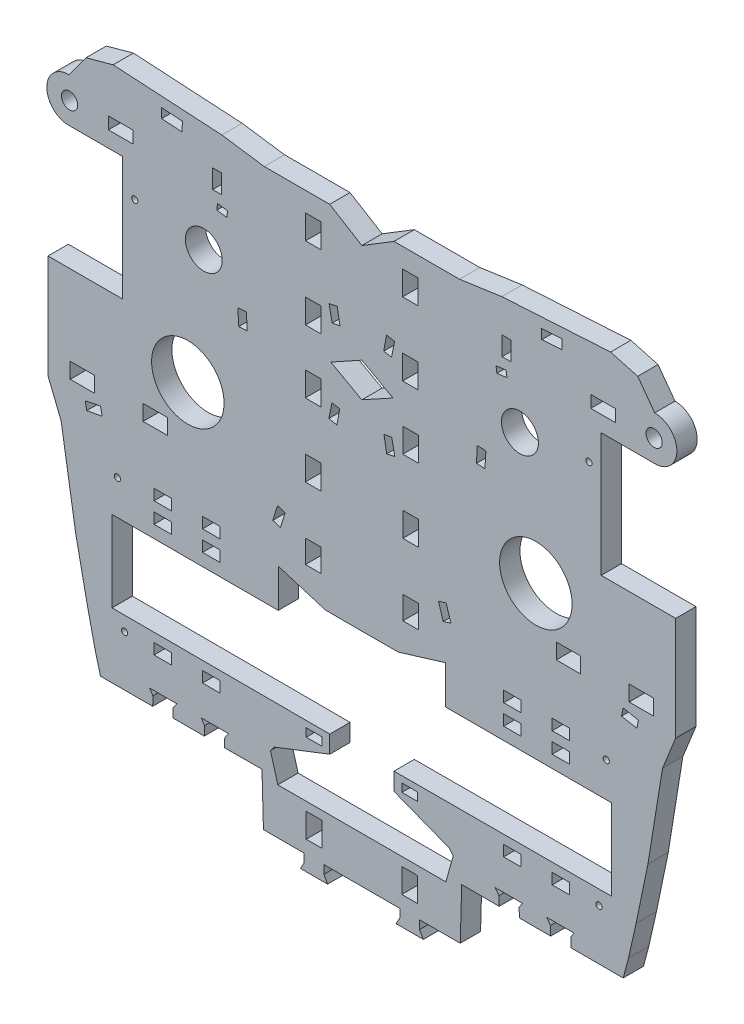
SolidWorks part; units mm, degrees
ref_plane "前视基准面" through (0, 0, 0) normal (0, 0, 1) x (1, 0, 0)
ref_plane "上视基准面" through (0, 0, 0) normal (0, 1, 0) x (1, 0, 0)
ref_plane "右视基准面" through (0, 0, 0) normal (1, 0, 0) x (0, 0, -1)
sketch "草图2" plane through (0, 0, 0) normal (0, 0, 1) x (1, 0, 0)
  line L0 (28.9762, 65.0478) -> (34.5335, 67.9669)
  line L1 (22.1059, 53.5065) -> (22.3713, 56.3476)
  line L2 (22.3713, 56.3476) -> (22.3796, 56.4328)
  line L3 (-126.8715, 84.3449) -> (-126.4029, 84.2212)
  line L4 (-123.6512, 83.7869) -> (-120.2718, 84.9928)
  line L5 (-122.6592, 71.7851) -> (-124.331, 76.7437)
  line L6 (-124.7598, 78.0157) -> (-126.8715, 84.3449)
  line L7 (-122.6456, 71.7449) -> (-122.6592, 71.7851)
  line L8 (-120.2718, 84.9928) -> (-121.3344, 90.9619)
  line L9 (-172.426, 53.3744) -> (-172.7131, 56.2698)
  line L10 (-172.7131, 56.2698) -> (-170.4704, 60.2847)
  line L11 (-121.0245, 56.0676) -> (-120.8497, 56.0045)
  line L12 (-192.6376, 71.9713) -> (-191.7183, 71.4889)
  line L13 (-184.2398, 59.5928) -> (-184.1723, 59.6254)
  line L14 (-128.0961, 112.0963) -> (-126.0764, 111.9125)
  line L15 (-126.0764, 111.9125) -> (-124.0748, 111.7182)
  line L16 (-127.4224, 122.0158) -> (-127.3955, 121.9925)
  line L17 (-142.7265, -15.9399) -> (-141.1862, -16.0473)
  line L18 (-177.9396, -21.8126) -> (-179.5584, -19.3492)
  line L19 (-22.969, -105.6053) -> (-22.2456, -105.6053)
  line L20 (-22.9681, -115.3686) -> (-22.2447, -115.3685)
  line L21 (-30.138, 84.9998) -> (-26.3049, 83.6324)
  line L22 (-26.9201, 121.6538) -> (-24.9619, 121.825)
  line L23 (-24.9619, 121.825) -> (-23.0081, 121.9957)
  line L24 (-26.6991, 105.0832) -> (-26.6824, 105.3641)
  line L25 (10.0876, 3.4791) -> (13.5686, 3.8223)
  line L26 (17.5014, -21.863) -> (17.6127, -26.3599)
  line L27 (22.7017, 33.9401) -> (19.9976, 36.1588)
  line L28 (78.899, -10.2754) -> (78.8942, 40.7872)
  line L29 (20.0003, 6.4871) -> (22.704, 8.7064)
  line L30 (13.5653, 38.8224) -> (10.0843, 39.165)
  line L31 (10.0843, 39.165) -> (6.6034, 38.8218)
  line L32 (27.5857, 24.8047) -> (26.57, 28.1518)
  line L33 (-7.4124, 24.8014) -> (-6.3973, 28.1487)
  line L34 (10.0876, 3.4791) -> (6.6087, 3.8216)
  line L35 (19.9976, 36.1588) -> (16.9126, 37.8074)
  line L36 (-2.5277, 8.704) -> (-4.7469, 11.4077)
  line L37 (26.5713, 14.4954) -> (27.5864, 17.8427)
  line L38 (67.9219, -6.3221) -> (67.952, 1.3547)
  line L39 (32.0763, -6.3255) -> (32.1064, 1.3513)
  line L40 (52.2258, -14.2164) -> (53.0488, -10.2507)
  line L41 (-7.4124, 24.8014) -> (-7.757, 21.3204)
  line L42 (56.0239, 1.3657) -> (67.952, 1.3547)
  line L43 (3.2583, 37.8061) -> (6.6034, 38.8218)
  line L44 (0.1764, 6.4853) -> (-2.5277, 8.704)
  line L45 (56.0023, -6.3112) -> (67.9219, -6.3221)
  line L46 (-2.5321, 33.9377) -> (-4.7508, 31.2337)
  line L47 (16.9157, 4.838) -> (20.0003, 6.4871)
  line L48 (0.1764, 6.4853) -> (3.2593, 4.8367)
  line L49 (59.8407, -15.6028) -> (60.5375, -11.7652)
  line L50 (26.57, 28.1518) -> (24.9209, 31.2364)
  line L51 (27.9289, 21.3237) -> (27.5857, 24.8047)
  line L52 (17.5014, -21.863) -> (15.6272, -19.338)
  line L53 (3.2593, 4.8367) -> (6.6087, 3.8216)
  line L54 (13.5686, 3.8223) -> (16.9157, 4.838)
  line L55 (-7.4138, 17.8394) -> (-6.3981, 14.4923)
  line L56 (-6.3981, 14.4923) -> (-4.7469, 11.4077)
  line L57 (-7.4138, 17.8394) -> (-7.757, 21.3204)
  line L58 (20.1567, -6.3145) -> (32.0763, -6.3255)
  line L59 (59.8407, -15.6028) -> (52.2258, -14.2164)
  line L60 (60.5375, -11.7652) -> (53.0488, -10.2507)
  line L61 (24.9209, 31.2364) -> (22.7017, 33.9401)
  line L62 (0.1716, 36.157) -> (-2.5321, 33.9377)
  line L63 (16.9126, 37.8074) -> (13.5653, 38.8224)
  line L64 (56.0239, 1.3657) -> (56.0023, -6.3112)
  line L65 (20.1763, 1.3624) -> (20.1567, -6.3145)
  line L66 (27.4583, -21.7998) -> (29.0766, -19.3363)
  line L67 (24.9228, 11.4104) -> (26.5713, 14.4954)
  line L68 (27.5864, 17.8427) -> (27.9289, 21.3237)
  line L69 (62.6768, -21.7972) -> (64.295, -19.333)
  line L70 (22.704, 8.7064) -> (24.9228, 11.4104)
  line L71 (52.8311, -26.3567) -> (52.7218, -21.8597)
  line L72 (50.8435, -19.3348) -> (52.7218, -21.8597)
  line L73 (20.1763, 1.3624) -> (32.1064, 1.3513)
  line L74 (3.2583, 37.8061) -> (0.1716, 36.157)
  line L75 (-4.7508, 31.2337) -> (-6.3973, 28.1487)
  line L76 (78.8942, 40.7872) -> (42.2483, 40.7838)
  line L77 (-10.2014, -6.0603) -> (-11.6066, 0.436)
  line L78 (-11.6066, 0.436) -> (-20.8211, 2.8937)
  line L79 (-2.5746, -17.3208) -> (-3.8808, -3.9467)
  line L80 (42.2433, 71.9867) -> (42.2483, 40.7838)
  line L81 (-20.8211, 2.8937) -> (-28.108, 16.52)
  line L82 (-28.108, 16.52) -> (-34.6449, 31.522)
  line L83 (-4.1943, -4.1998) -> (-3.8808, -3.9467)
  line L84 (72.4196, -26.3548) -> (78.899, -10.2754)
  line L85 (31.1655, 61.1182) -> (28.9762, 65.0478)
  line L86 (34.0007, 59.7551) -> (31.1655, 61.1182)
  line L87 (-2.5746, -17.3208) -> (-2.9271, -17.1084)
  line L88 (-10.2014, -6.0603) -> (-6.4257, -5.8106)
  line L89 (-161.4887, 79.6451) -> (-161.7243, 81.4118)
  line L90 (-127.2073, 45.8008) -> (-122.7956, 58.4544)
  line L91 (-124.0916, 83.6298) -> (-123.8115, 83.7294)
  line L92 (-225.6169, 121.0265) -> (-218.9733, 123.182)
  line L93 (-131.6572, 65.6852) -> (-131.2414, 57.8197)
  line L94 (-131.6138, 65.689) -> (-131.2414, 57.8197)
  line L95 (-131.6138, 65.689) -> (-131.6572, 65.6852)
  line L96 (-144.9103, 76.9359) -> (-144.1247, 78.5356)
  line L97 (-143.7881, 83.8033) -> (-144.3637, 85.49)
  line L98 (-122.6151, 71.657) -> (-122.6456, 71.7449)
  line L99 (-219.8689, 101.5544) -> (-192.6404, 101.5569)
  line L100 (-143.734, 135.1135) -> (-197.2651, 138.2573)
  line L101 (-122.9113, 132.1263) -> (-143.734, 135.1135)
  line L102 (-129.7999, 124.0246) -> (-129.7958, 124.0912)
  line L103 (-121.3344, 90.9619) -> (-123.7019, 105.0742)
  line L104 (-115.7691, 65.1023) -> (-117.1585, 75.4988)
  line L105 (-117.3459, 54.7409) -> (-115.7691, 65.1023)
  line L106 (-120.4169, 45.2631) -> (-124.1315, 46.6288)
  line L107 (-121.6067, 39.3244) -> (-120.4169, 45.2631)
  line L108 (-146.2385, 101.8438) -> (-141.2982, 101.1876)
  line L109 (-145.8589, 104.8567) -> (-146.2385, 101.8438)
  line L110 (-135.9056, 65.4357) -> (-131.6572, 65.6852)
  line L111 (-135.3876, 57.6297) -> (-135.9056, 65.4357)
  line L112 (-173.3789, 127.2909) -> (-173.3228, 131.9672)
  line L113 (-163.3961, 126.5967) -> (-173.3789, 127.2909)
  line L114 (-148.2705, 118.8854) -> (-143.8623, 118.8858)
  line L115 (-148.2705, 118.8854) -> (-148.2697, 109.5965)
  line L116 (-143.8614, 109.5969) -> (-148.2697, 109.5965)
  line L117 (-187.5112, 109.3753) -> (-199.5962, 109.3742)
  line L118 (-199.5967, 115.3302) -> (-187.5117, 115.3314)
  line L119 (-199.5962, 109.3742) -> (-199.5967, 115.3302)
  line L120 (-187.1638, 87.5363) -> (-186.5809, 87.646)
  line L121 (-187.6607, 87.212) -> (-187.1638, 87.5363)
  line L122 (-187.9955, 86.7226) -> (-187.6607, 87.212)
  line L123 (-188.1171, 86.1427) -> (-187.9955, 86.7226)
  line L124 (-188.1171, 86.1427) -> (-188.0071, 85.556)
  line L125 (-188.0071, 85.556) -> (-187.6822, 85.0644)
  line L126 (-187.6822, 85.0644) -> (-187.1919, 84.736)
  line L127 (-186.6112, 84.624) -> (-187.1919, 84.736)
  line L128 (-157.9459, 89.1056) -> (-156.4037, 89.9994)
  line L129 (-159.2838, 87.9283) -> (-157.9459, 89.1056)
  line L130 (-160.3664, 86.5125) -> (-159.2838, 87.9283)
  line L131 (-161.1521, 84.9128) -> (-160.3664, 86.5125)
  line L132 (-161.6106, 83.1904) -> (-161.1521, 84.9128)
  line L133 (-161.7243, 81.4118) -> (-161.6106, 83.1904)
  line L134 (-160.9131, 77.9584) -> (-161.4887, 79.6451)
  line L135 (-160.0194, 76.4164) -> (-160.9131, 77.9584)
  line L136 (-158.8421, 75.0783) -> (-160.0194, 76.4164)
  line L137 (-157.4263, 73.9956) -> (-158.8421, 75.0783)
  line L138 (-155.8265, 73.21) -> (-157.4263, 73.9956)
  line L139 (-154.1042, 72.7515) -> (-155.8265, 73.21)
  line L140 (-152.3258, 72.6379) -> (-154.1042, 72.7515)
  line L141 (-154.7169, 90.575) -> (-152.9506, 90.8105)
  line L142 (-156.4037, 89.9994) -> (-154.7169, 90.575)
  line L143 (-192.6376, 71.9713) -> (-192.6404, 101.5569)
  line L144 (-181.4503, 60.9383) -> (-179.2154, 64.9275)
  line L145 (-120.7755, 74.1747) -> (-117.1585, 75.4988)
  line L146 (-122.6151, 71.657) -> (-120.7755, 74.1747)
  line L147 (-210.6198, 134.5936) -> (-197.2651, 138.2573)
  line L148 (-210.6198, 134.5936) -> (-218.9733, 123.182)
  line L149 (-229.2104, 116.5805) -> (-225.6169, 121.0265)
  line L150 (-229.2104, 116.5805) -> (-230.4465, 112.3503)
  line L151 (-228.9806, 107.8824) -> (-230.4465, 112.3503)
  line L152 (-225.9221, 104.047) -> (-228.9806, 107.8824)
  line L153 (-219.8689, 101.5544) -> (-225.9221, 104.047)
  line L154 (-141.2982, 101.1876) -> (-140.9191, 104.232)
  line L155 (-140.9191, 104.232) -> (-145.8589, 104.8567)
  line L156 (-135.3876, 57.6297) -> (-135.9413, 65.4418)
  line L157 (-173.3228, 131.9672) -> (-163.1284, 131.2535)
  line L158 (-163.3961, 126.5967) -> (-163.1284, 131.2535)
  line L159 (-143.8623, 118.8858) -> (-143.8614, 109.5969)
  line L160 (-185.5099, 87.1906) -> (-186.0002, 87.5247)
  line L161 (-185.185, 86.7003) -> (-185.5099, 87.1906)
  line L162 (-185.0749, 86.1273) -> (-185.185, 86.7003)
  line L163 (-185.1966, 85.554) -> (-185.0749, 86.1273)
  line L164 (-185.5313, 85.0684) -> (-185.1966, 85.554)
  line L165 (-186.0283, 84.7404) -> (-185.5313, 85.0684)
  line L166 (-186.6112, 84.624) -> (-186.0283, 84.7404)
  line L167 (-186.0002, 87.5247) -> (-186.5809, 87.646)
  line L168 (-151.1726, 90.6969) -> (-152.9506, 90.8105)
  line L169 (-149.4504, 90.2383) -> (-151.1726, 90.6969)
  line L170 (-147.8506, 89.4527) -> (-149.4504, 90.2383)
  line L171 (-146.4347, 88.3702) -> (-147.8506, 89.4527)
  line L172 (-145.2575, 87.032) -> (-146.4347, 88.3702)
  line L173 (-144.3637, 85.49) -> (-145.2575, 87.032)
  line L174 (-143.5525, 82.0367) -> (-143.7881, 83.8033)
  line L175 (-143.6662, 80.2579) -> (-143.5525, 82.0367)
  line L176 (-144.1247, 78.5356) -> (-143.6662, 80.2579)
  line L177 (-145.9929, 75.5201) -> (-144.9103, 76.9359)
  line L178 (-147.331, 74.3427) -> (-145.9929, 75.5201)
  line L179 (-148.873, 73.4491) -> (-147.331, 74.3427)
  line L180 (-150.5598, 72.8733) -> (-148.873, 73.4491)
  line L181 (-152.3258, 72.6379) -> (-150.5598, 72.8733)
  line L182 (-187.5112, 109.3753) -> (-187.5117, 115.3314)
  line L183 (-135.9056, 65.4357) -> (-135.9413, 65.4418)
  line L184 (-215.2212, 114.316) -> (-214.8216, 113.3513)
  line L185 (-215.2209, 110.316) -> (-215.8565, 109.4875)
  line L186 (-219.7201, 108.4519) -> (-220.6848, 108.8514)
  line L187 (-220.6848, 108.8514) -> (-221.5133, 109.487)
  line L188 (-221.5139, 115.1439) -> (-220.6855, 115.7796)
  line L189 (-222.6852, 112.3153) -> (-222.549, 113.3506)
  line L190 (-218.6855, 116.3157) -> (-218.4324, 116.2717)
  line L191 (-217.6495, 108.4521) -> (-218.6848, 108.3157)
  line L192 (-217.6502, 116.1795) -> (-216.6855, 115.78)
  line L193 (-214.6852, 112.3161) -> (-214.8214, 111.2808)
  line L194 (-214.8214, 111.2808) -> (-215.2209, 110.316)
  line L195 (-216.6848, 108.8518) -> (-217.6495, 108.4521)
  line L196 (-221.5133, 109.487) -> (-222.1491, 110.3154)
  line L197 (-222.1491, 110.3154) -> (-222.5488, 111.2801)
  line L198 (-222.5488, 111.2801) -> (-222.6852, 112.3153)
  line L199 (-222.1494, 114.3154) -> (-221.5139, 115.1439)
  line L200 (-218.4324, 116.2717) -> (-217.6502, 116.1795)
  line L201 (-218.9379, 108.3596) -> (-219.7201, 108.4519)
  line L202 (-218.6848, 108.3157) -> (-218.9379, 108.3596)
  line L203 (-215.8565, 109.4875) -> (-216.6848, 108.8518)
  line L204 (-220.6855, 115.7796) -> (-219.7208, 116.1793)
  line L205 (-216.6855, 115.78) -> (-215.857, 115.1444)
  line L206 (-222.549, 113.3506) -> (-222.1494, 114.3154)
  line L207 (-214.8216, 113.3513) -> (-214.6852, 112.3161)
  line L208 (-219.7208, 116.1793) -> (-218.6855, 116.3157)
  line L209 (-215.857, 115.1444) -> (-215.2212, 114.316)
  line L210 (-94.8976, 19.6661) -> (-102.5745, 19.6962)
  line L211 (-75.1138, 5.2024) -> (-75.1114, -20.2233)
  line L212 (-81.8835, -18.7264) -> (-81.8818, -32.1778)
  line L213 (-126.8679, 45.9059) -> (-126.0266, 46.1282)
  line L214 (-141.8519, -26.4872) -> (-140.7595, -16.077)
  line L215 (-138.3487, 0.3423) -> (-129.1501, 2.7906)
  line L216 (-122.6495, 58.5353) -> (-120.8497, 56.0045)
  line L217 (-115.5853, 65.1266) -> (-90.0553, 65.129)
  line L218 (-79.42, -20.3446) -> (-81.8835, -18.7264)
  line L219 (-121.9382, 16.234) -> (-115.2905, 31.4252)
  line L220 (-94.9456, -27.4007) -> (-94.9467, -16.1128)
  line L221 (-143.7843, -5.8873) -> (-139.7568, -6.1605)
  line L222 (-143.7843, -5.8873) -> (-143.8642, -5.8228)
  line L223 (-75.1181, 56.46) -> (-90.0553, 65.129)
  line L224 (-102.5845, 7.7661) -> (-102.5745, 19.6962)
  line L225 (-94.9086, 7.7466) -> (-102.5845, 7.7661)
  line L226 (-116.2334, -9.1175) -> (-118.5436, -16.5886)
  line L227 (-114.7748, -17.754) -> (-118.5436, -16.5886)
  line L228 (-94.912, 43.5922) -> (-102.5879, 43.6117)
  line L229 (-102.5769, 55.5418) -> (-94.901, 55.5118)
  line L230 (-102.5879, 43.6117) -> (-102.5769, 55.5418)
  line L231 (-90.9719, 40.6367) -> (-89.457, 48.1272)
  line L232 (-87.0066, 39.8138) -> (-90.9719, 40.6367)
  line L233 (-102.5082, -27.4556) -> (-102.5093, -16.1107)
  line L234 (-94.9456, -27.4007) -> (-102.5082, -27.4556)
  line L235 (-75.1181, 56.46) -> (-75.118, 50.3879)
  line L236 (-94.9086, 7.7466) -> (-94.8976, 19.6661)
  line L237 (-115.2905, 31.4252) -> (-121.3358, 39.2795)
  line L238 (-81.8868, 16.6664) -> (-81.8851, 3.2149)
  line L239 (-79.4233, 15.0481) -> (-81.8868, 16.6664)
  line L240 (-75.117, 40.4209) -> (-75.1147, 15.1695)
  line L241 (-79.3634, 40.3096) -> (-75.117, 40.4209)
  line L242 (-81.8901, 51.8848) -> (-81.8884, 38.4334)
  line L243 (-79.4266, 50.2666) -> (-81.8901, 51.8848)
  line L244 (-75.118, 50.3879) -> (-79.4266, 50.2666)
  line L245 (-117.1385, 54.6627) -> (-115.5853, 65.1266)
  line L246 (-121.3358, 39.2795) -> (-120.2668, 45.2518)
  line L247 (-129.1501, 2.7906) -> (-121.9382, 16.234)
  line L248 (-139.7568, -6.1605) -> (-138.3487, 0.3423)
  line L249 (-144.6936, -15.8028) -> (-147.3897, -17.4236)
  line L250 (-92.7425, -41.8399) -> (-141.8519, -26.4872)
  line L251 (-75.1094, -41.9181) -> (-92.7425, -41.8399)
  line L252 (-75.1104, -30.1903) -> (-75.1094, -41.9181)
  line L253 (-79.3568, -30.3015) -> (-75.1104, -30.1903)
  line L254 (-112.4514, -10.287) -> (-116.2334, -9.1175)
  line L255 (-114.7748, -17.754) -> (-112.4514, -10.287)
  line L256 (-94.912, 43.5922) -> (-94.901, 55.5118)
  line L257 (-85.6204, 47.4305) -> (-89.457, 48.1272)
  line L258 (-87.0066, 39.8138) -> (-85.6204, 47.4305)
  line L259 (-94.9467, -16.1128) -> (-102.5093, -16.1107)
  line L260 (-23.4311, 45.9156) -> (-26.1826, 46.6418)
  line L261 (-55.3867, 43.5959) -> (-47.7098, 43.6168)
  line L262 (-75.1094, -41.9181) -> (-57.5392, -41.8367)
  line L263 (-47.7098, 43.6168) -> (-47.7231, 55.5469)
  line L264 (-35.5115, -17.7466) -> (-37.8362, -10.28)
  line L265 (-59.3253, 40.6396) -> (-60.8416, 48.13)
  line L266 (-33.1613, 54.6706) -> (-34.7164, 65.1341)
  line L267 (-8.4336, -26.4747) -> (-57.5392, -41.8367)
  line L268 (-9.5281, -16.0648) -> (-8.4336, -26.4747)
  line L269 (-2.8975, -17.4102) -> (-5.594, -15.7899)
  line L270 (-10.5326, -6.1487) -> (-6.5052, -5.8748)
  line L271 (-11.9419, 0.3541) -> (-10.5326, -6.1487)
  line L272 (-21.1409, 2.8007) -> (-11.9419, 0.3541)
  line L273 (-28.3554, 16.2427) -> (-21.1409, 2.8007)
  line L274 (-35.0059, 31.4327) -> (-28.3554, 16.2427)
  line L275 (-28.962, 39.2881) -> (-35.0059, 31.4327)
  line L276 (-30.0322, 45.2602) -> (-28.962, 39.2881)
  line L277 (-75.1181, 56.46) -> (-60.2473, 65.1315)
  line L278 (-55.3999, 55.5154) -> (-55.3867, 43.5959)
  line L279 (-47.7231, 55.5469) -> (-55.3999, 55.5154)
  line L280 (-34.0546, -9.1096) -> (-37.8362, -10.28)
  line L281 (-34.0546, -9.1096) -> (-31.7429, -16.5805)
  line L282 (-35.5115, -17.7466) -> (-31.7429, -16.5805)
  line L283 (-55.3833, 7.7502) -> (-47.7065, 7.7712)
  line L284 (-55.3965, 19.6698) -> (-55.3833, 7.7502)
  line L285 (-47.7197, 19.7013) -> (-55.3965, 19.6698)
  line L286 (-47.7065, 7.7712) -> (-47.7197, 19.7013)
  line L287 (-64.679, 47.4325) -> (-63.2913, 39.8158)
  line L288 (-60.8416, 48.13) -> (-64.679, 47.4325)
  line L289 (-63.2913, 39.8158) -> (-59.3253, 40.6396)
  line L290 (-55.3398, -27.3969) -> (-47.7762, -27.4505)
  line L291 (-55.3408, -16.1089) -> (-55.3398, -27.3969)
  line L292 (-47.7773, -16.1053) -> (-55.3408, -16.1089)
  line L293 (-47.7762, -27.4505) -> (-47.7773, -16.1053)
  line L294 (-34.7164, 65.1341) -> (-34.82, 65.1341)
  line L295 (-2.9271, -17.1084) -> (-4.1943, -4.1998)
  line L296 (-23.4311, 45.9156) -> (-27.6139, 58.4332)
  line L297 (-9.5281, -16.0648) -> (-9.1917, -16.0413)
  line L298 (-177.0863, -97.8629) -> (-168.4788, -97.8621)
  line L299 (-197.7451, -93.4502) -> (-123.9545, -93.4433)
  line L300 (-192.1158, -99.1269) -> (-191.533, -99.0109)
  line L301 (-168.4783, -103.2033) -> (-177.0858, -103.2041)
  line L302 (-166.107, -19.3484) -> (-167.9829, -21.8738)
  line L303 (-152.2175, -120.8342) -> (-152.3379, -125.3933)
  line L304 (-192.6109, -101.6126) -> (-192.1164, -101.9429)
  line L305 (-123.9525, -115.3715) -> (-123.9515, -125.289)
  line L306 (-144.6051, -103.2011) -> (-153.2125, -103.2019)
  line L307 (-213.2785, -26.375) -> (-213.158, -21.8159)
  line L308 (-177.6084, -120.8365) -> (-177.7289, -125.3957)
  line L309 (-131.4024, -103.7923) -> (-131.4011, -117.2184)
  line L310 (-167.7621, -125.3947) -> (-167.6517, -120.8977)
  line L311 (-190.1252, -101.118) -> (-190.0093, -100.5347)
  line L312 (-142.3712, -125.3924) -> (-142.2607, -120.8954)
  line L313 (-177.0933, -32.1584) -> (-168.4849, -32.1576)
  line L314 (-197.7451, -93.4502) -> (-197.7488, -53.622)
  line L315 (-123.9536, -93.6578) -> (-123.9545, -93.4433)
  line L316 (-144.6051, -103.2011) -> (-144.6056, -97.8599)
  line L317 (-177.6084, -120.8365) -> (-179.2264, -118.3732)
  line L318 (-222.7955, -26.3759) -> (-213.2785, -26.375)
  line L319 (-140.3849, -118.37) -> (-153.8362, -118.3708)
  line L320 (-177.0863, -97.8629) -> (-177.0858, -103.2041)
  line L321 (-177.7289, -125.3957) -> (-203.4233, -125.4246)
  line L322 (-213.158, -21.8159) -> (-214.7768, -19.3525)
  line L323 (-123.9534, -105.6083) -> (-128.1155, -105.6087)
  line L324 (-201.3255, -19.3517) -> (-203.2004, -21.8771)
  line L325 (-215.6151, -70.7366) -> (-222.7955, -26.3759)
  line L326 (-152.3379, -125.3933) -> (-167.7621, -125.3947)
  line L327 (-203.4233, -125.4246) -> (-206.0364, -115.5923)
  line L328 (-167.6517, -120.8977) -> (-165.7759, -118.3723)
  line L329 (-153.8362, -118.3708) -> (-152.2175, -120.8342)
  line L330 (-142.2607, -120.8954) -> (-140.3849, -118.37)
  line L331 (-177.0928, -37.4996) -> (-168.4844, -37.4988)
  line L332 (-178.0601, -26.3717) -> (-177.9396, -21.8126)
  line L333 (-168.4849, -32.1576) -> (-168.4844, -37.4988)
  line L334 (-203.207, -26.3741) -> (-203.3118, -26.3741)
  line L335 (-128.1146, -115.3719) -> (-123.9525, -115.3715)
  line L336 (-167.9829, -21.8738) -> (-168.0934, -26.3708)
  line L337 (-168.4783, -103.2033) -> (-168.4788, -97.8621)
  line L338 (-123.9515, -125.289) -> (-142.3712, -125.3924)
  line L339 (-192.6109, -101.6126) -> (-192.9403, -101.1182)
  line L340 (-167.9886, -26.3708) -> (-168.0934, -26.3708)
  line L341 (-115.9512, -53.6146) -> (-115.9538, -34.7661)
  line L342 (-197.7488, -53.622) -> (-115.9512, -53.6146)
  line L343 (-144.6112, -37.4966) -> (-153.2196, -37.4974)
  line L344 (-190.4556, -101.6124) -> (-190.1252, -101.118)
  line L345 (-179.2264, -118.3732) -> (-165.7759, -118.3723)
  line L346 (-177.0928, -37.4996) -> (-177.0933, -32.1584)
  line L347 (-153.2187, -47.5201) -> (-144.6103, -47.5193)
  line L348 (-153.214, -97.8607) -> (-153.2125, -103.2019)
  line L349 (-215.6151, -70.7366) -> (-209.7899, -98.9452)
  line L350 (-153.214, -97.8607) -> (-144.6056, -97.8599)
  line L351 (-153.2192, -32.1562) -> (-153.2196, -37.4974)
  line L352 (-192.9405, -99.9518) -> (-192.6101, -99.4573)
  line L353 (-206.0364, -115.5923) -> (-209.7899, -98.9452)
  line L354 (-193.0564, -100.535) -> (-192.9405, -99.9518)
  line L355 (-144.6117, -32.1554) -> (-153.2192, -32.1562)
  line L356 (-144.6112, -37.4966) -> (-144.6117, -32.1554)
  line L357 (-196.1887, -35.5254) -> (-196.519, -36.0199)
  line L358 (-153.2192, -42.1789) -> (-144.6108, -42.1781)
  line L359 (-191.5327, -102.0588) -> (-192.1164, -101.9429)
  line L360 (-190.4558, -99.4571) -> (-190.9503, -99.1268)
  line L361 (-194.0332, -37.6805) -> (-193.7029, -37.1861)
  line L362 (-192.6101, -99.4573) -> (-192.1158, -99.1269)
  line L363 (-196.1875, -37.6807) -> (-196.518, -37.1863)
  line L364 (-153.2192, -42.1789) -> (-153.2187, -47.5201)
  line L365 (-196.634, -36.6031) -> (-196.519, -36.0199)
  line L366 (-194.0334, -35.5252) -> (-194.5278, -35.1949)
  line L367 (-190.1253, -99.9515) -> (-190.4558, -99.4571)
  line L368 (-191.5327, -102.0588) -> (-190.95, -101.9428)
  line L369 (-194.5275, -38.0109) -> (-194.0332, -37.6805)
  line L370 (-193.5869, -36.6028) -> (-193.703, -36.0196)
  line L371 (-177.091, -47.5224) -> (-177.0915, -42.1811)
  line L372 (-192.9403, -101.1182) -> (-193.0564, -100.535)
  line L373 (-195.1108, -38.127) -> (-194.5275, -38.0109)
  line L374 (-190.95, -101.9428) -> (-190.4556, -101.6124)
  line L375 (-144.6103, -47.5193) -> (-144.6108, -42.1781)
  line L376 (-168.4834, -47.5216) -> (-168.4839, -42.1803)
  line L377 (-195.1111, -35.0789) -> (-195.6943, -35.195)
  line L378 (-193.7029, -37.1861) -> (-193.5869, -36.6028)
  line L379 (-196.634, -36.6031) -> (-196.518, -37.1863)
  line L380 (-195.1108, -38.127) -> (-195.6931, -38.011)
  line L381 (-195.6943, -35.195) -> (-196.1887, -35.5254)
  line L382 (-193.703, -36.0196) -> (-194.0334, -35.5252)
  line L383 (-195.6931, -38.011) -> (-196.1875, -37.6807)
  line L384 (-177.091, -47.5224) -> (-168.4834, -47.5216)
  line L385 (-191.533, -99.0109) -> (-190.9503, -99.1268)
  line L386 (-190.0093, -100.5347) -> (-190.1253, -99.9515)
  line L387 (-195.1111, -35.0789) -> (-194.5278, -35.1949)
  line L388 (-177.0915, -42.1811) -> (-168.4839, -42.1803)
  line L389 (39.6472, -100.5198) -> (39.7632, -101.103)
  line L390 (26.7246, -97.8504) -> (18.1161, -97.8512)
  line L391 (47.3817, -93.4338) -> (-26.408, -93.4407)
  line L392 (41.7543, -99.1116) -> (41.1711, -98.9956)
  line L393 (-19.6825, -104.1884) -> (-18.9591, -103.7885)
  line L394 (-7.9863, -125.3863) -> (-8.0975, -120.8893)
  line L395 (18.1166, -103.1924) -> (26.7251, -103.1916)
  line L396 (-26.406, -125.2864) -> (-26.4069, -115.3689)
  line L397 (17.2934, -120.887) -> (17.4047, -125.3839)
  line L398 (1.9808, -125.3854) -> (1.8594, -120.8261)
  line L399 (-5.7565, -103.1946) -> (2.8519, -103.1938)
  line L400 (17.6062, -21.863) -> (15.7299, -19.338)
  line L401 (41.7546, -101.9276) -> (42.2489, -101.5972)
  line L402 (-18.9579, -117.2144) -> (-18.9591, -103.7885)
  line L403 (27.3717, -125.383) -> (27.2503, -120.8238)
  line L404 (47.378, -53.6059) -> (47.3817, -93.4338)
  line L405 (18.11, -32.1467) -> (26.7185, -32.1459)
  line L406 (-26.4078, -105.6057) -> (-26.408, -93.4407)
  line L407 (-5.7565, -103.1946) -> (-5.7561, -97.8534)
  line L408 (53.0659, -125.4072) -> (55.6771, -115.5744)
  line L409 (27.2503, -120.8238) -> (28.8685, -118.3603)
  line L410 (50.9483, -19.3347) -> (64.295, -19.333)
  line L411 (-8.0975, -120.8893) -> (-9.9738, -118.3644)
  line L412 (27.3717, -125.383) -> (53.0659, -125.4072)
  line L413 (65.2484, -70.7169) -> (72.4196, -26.3548)
  line L414 (52.8246, -21.8597) -> (50.9483, -19.3347)
  line L415 (-9.9738, -118.3644) -> (3.4776, -118.3626)
  line L416 (15.4171, -118.362) -> (17.2934, -120.887)
  line L417 (1.9808, -125.3854) -> (17.4047, -125.3839)
  line L418 (26.719, -37.4871) -> (18.1114, -37.4879)
  line L419 (1.8594, -120.8261) -> (3.4776, -118.3626)
  line L420 (26.7251, -103.1916) -> (26.7246, -97.8504)
  line L421 (-18.9579, -117.2144) -> (-19.6813, -116.8081)
  line L422 (18.11, -32.1467) -> (18.1114, -37.4879)
  line L423 (-22.9681, -115.3686) -> (-26.4069, -115.3689)
  line L424 (17.718, -26.3599) -> (17.6127, -26.3599)
  line L425 (18.1166, -103.1924) -> (18.1161, -97.8512)
  line L426 (65.2484, -70.7169) -> (59.4275, -98.9266)
  line L427 (17.718, -26.3599) -> (17.6062, -21.863)
  line L428 (-26.406, -125.2864) -> (-7.9863, -125.3863)
  line L429 (-5.7632, -32.1489) -> (2.8452, -32.1481)
  line L430 (42.2489, -101.5972) -> (42.5793, -101.1027)
  line L431 (-34.4187, -53.6135) -> (-34.4205, -34.7652)
  line L432 (47.378, -53.6059) -> (-34.4187, -53.6135)
  line L433 (15.7299, -19.338) -> (29.0766, -19.3363)
  line L434 (40.0946, -101.5974) -> (39.7632, -101.103)
  line L435 (55.6771, -115.5744) -> (59.4275, -98.9266)
  line L436 (28.8685, -118.3603) -> (15.4171, -118.362)
  line L437 (26.719, -37.4871) -> (26.7185, -32.1459)
  line L438 (2.8467, -47.5121) -> (-5.7608, -47.5129)
  line L439 (2.8514, -97.8526) -> (-5.7561, -97.8534)
  line L440 (2.8519, -103.1938) -> (2.8514, -97.8526)
  line L441 (2.8452, -32.1481) -> (2.8457, -37.4893)
  line L442 (42.5792, -99.9363) -> (42.2487, -99.4419)
  line L443 (42.6952, -100.5195) -> (42.5792, -99.9363)
  line L444 (52.9358, -26.3567) -> (52.8311, -26.3567)
  line L445 (-5.7627, -37.4901) -> (2.8457, -37.4893)
  line L446 (-5.7627, -37.4901) -> (-5.7632, -32.1489)
  line L447 (-5.7622, -42.1716) -> (2.8462, -42.1708)
  line L448 (18.1109, -42.1694) -> (18.1114, -47.5106)
  line L449 (45.8144, -35.5093) -> (46.1449, -36.0037)
  line L450 (41.1713, -102.0437) -> (41.7546, -101.9276)
  line L451 (40.0944, -99.4421) -> (40.5888, -99.1117)
  line L452 (43.3289, -37.1704) -> (43.6594, -37.6648)
  line L453 (42.2487, -99.4419) -> (41.7543, -99.1116)
  line L454 (45.8146, -37.6646) -> (46.145, -37.1702)
  line L455 (46.2609, -36.5869) -> (46.1449, -36.0037)
  line L456 (43.6601, -35.5095) -> (44.1544, -35.1791)
  line L457 (43.3288, -36.004) -> (43.2128, -36.5872)
  line L458 (39.7641, -99.9365) -> (40.0944, -99.4421)
  line L459 (41.1713, -102.0437) -> (40.5891, -101.9277)
  line L460 (43.6594, -37.6648) -> (44.1538, -37.9951)
  line L461 (2.8462, -42.1708) -> (2.8467, -47.5121)
  line L462 (44.1538, -37.9951) -> (44.737, -38.1111)
  line L463 (42.5793, -101.1027) -> (42.6952, -100.5195)
  line L464 (40.0946, -101.5974) -> (40.5891, -101.9277)
  line L465 (26.7208, -47.4832) -> (26.7199, -47.5098)
  line L466 (-5.7608, -47.5129) -> (-5.7622, -42.1716)
  line L467 (43.3289, -37.1704) -> (43.2128, -36.5872)
  line L468 (44.737, -38.1111) -> (45.3202, -37.995)
  line L469 (45.32, -35.179) -> (45.8144, -35.5093)
  line L470 (43.6601, -35.5095) -> (43.3288, -36.004)
  line L471 (18.1109, -42.1694) -> (26.7194, -42.1686)
  line L472 (39.7641, -99.9365) -> (39.6472, -100.5198)
  line L473 (45.3202, -37.995) -> (45.8146, -37.6646)
  line L474 (41.1711, -98.9956) -> (40.5888, -99.1117)
  line L475 (26.7199, -47.5098) -> (18.1114, -47.5106)
  line L476 (44.7367, -35.063) -> (45.32, -35.179)
  line L477 (44.1544, -35.1791) -> (44.7367, -35.063)
  line L478 (46.145, -37.1702) -> (46.2609, -36.5869)
  line L479 (-123.9534, -105.6083) -> (-123.9536, -93.6578)
  line L480 (-120.4891, -115.2652) -> (-116.8891, -128.0694)
  line L481 (-19.6813, -117.2081) -> (-22.9681, -115.3686)
  line L482 (-95.2663, -144.2855) -> (-102.9745, -144.2661)
  line L483 (-26.4078, -105.6057) -> (-27.1303, -105.5993)
  line L484 (-56.8912, -150.693) -> (-94.2092, -150.6965)
  line L485 (-48.1856, -132.3308) -> (-55.8952, -132.3623)
  line L486 (-19.6813, -116.8081) -> (-19.6825, -104.1884)
  line L487 (-22.969, -105.6053) -> (-19.6825, -103.7822)
  line L488 (-102.9765, -132.3513) -> (-102.9745, -144.2661)
  line L489 (-27.1261, -150.6902) -> (-27.1294, -115.3625)
  line L490 (-34.1913, -128.062) -> (-30.5937, -115.2571)
  line L491 (-95.2674, -132.3506) -> (-102.9765, -132.3513)
  line L492 (-55.8952, -132.3623) -> (-55.8941, -144.2608)
  line L493 (-55.8941, -144.2608) -> (-48.1724, -144.261)
  line L494 (-27.1303, -105.5993) -> (-27.1314, -93.6488)
  line L495 (-48.1724, -144.261) -> (-48.1856, -132.3308)
  line L496 (-95.2663, -144.2855) -> (-95.2674, -132.3506)
  line L497 (-27.1261, -150.6902) -> (-47.128, -150.6921)
  line L498 (-47.1267, -154.8543) -> (-47.128, -150.6921)
  line L499 (-91.3346, -93.6547) -> (-91.3338, -102.2578)
  line L500 (-105.7873, -158.1464) -> (-92.3614, -158.1451)
  line L501 (-55.898, -100.7714) -> (-55.8985, -96.7395)
  line L502 (-102.962, -100.7758) -> (-102.9624, -96.7438)
  line L503 (-58.7061, -158.142) -> (-45.2801, -158.1407)
  line L504 (-120.4891, -115.2652) -> (-118.6435, -112.8644)
  line L505 (-123.9536, -93.6578) -> (-91.3346, -93.6547)
  line L506 (-118.6435, -112.8644) -> (-91.3338, -102.2578)
  line L507 (-105.7873, -158.1464) -> (-103.972, -154.8595)
  line L508 (-59.7514, -102.2551) -> (-59.7522, -93.652)
  line L509 (-94.2088, -154.8587) -> (-92.3614, -158.1451)
  line L510 (-47.1267, -154.8543) -> (-45.2801, -158.1407)
  line L511 (-56.8908, -154.8552) -> (-56.8912, -150.693)
  line L512 (-95.2539, -96.7279) -> (-95.2414, -100.7755)
  line L513 (-103.9724, -150.6974) -> (-123.9492, -150.6992)
  line L514 (-48.1765, -100.7711) -> (-55.898, -100.7714)
  line L515 (-32.4389, -112.8563) -> (-59.7514, -102.2551)
  line L516 (-55.8985, -96.7395) -> (-48.1889, -96.7235)
  line L517 (-103.972, -154.8595) -> (-103.9724, -150.6974)
  line L518 (-94.2092, -150.6965) -> (-94.2088, -154.8587)
  line L519 (-27.1314, -93.6488) -> (-59.7522, -93.652)
  line L520 (-30.5937, -115.2571) -> (-32.4389, -112.8563)
  line L521 (-95.2414, -100.7755) -> (-102.962, -100.7758)
  line L522 (-58.7061, -158.142) -> (-56.8908, -154.8552)
  line L523 (-48.1765, -100.7711) -> (-48.1889, -96.7235)
  line L524 (-95.2539, -96.7279) -> (-102.9624, -96.7438)
  line L525 (-160.4687, 3.4697) -> (-163.9493, 3.8122)
  line L526 (-173.0879, 33.9283) -> (-170.3842, 36.1476)
  line L527 (-177.9706, 17.83) -> (-176.9549, 14.4829)
  line L528 (-170.3815, 6.4758) -> (-173.0856, 8.6946)
  line L529 (-163.9525, 38.8124) -> (-160.472, 39.1555)
  line L530 (-177.9703, 24.792) -> (-176.9552, 28.1393)
  line L531 (-142.9711, 24.7952) -> (-143.9868, 28.1424)
  line L532 (-160.4687, 3.4697) -> (-156.9882, 3.8129)
  line L533 (-170.3842, 36.1476) -> (-167.2996, 37.7967)
  line L534 (-147.8528, 8.6969) -> (-145.634, 11.401)
  line L535 (-167.9886, -26.3708) -> (-167.8781, -21.8738)
  line L536 (-218.3007, -6.3424) -> (-218.3322, 1.3344)
  line L537 (-156.9915, 38.813) -> (-160.472, 39.1555)
  line L538 (-182.4875, 1.3378) -> (-182.456, -6.339)
  line L539 (-202.602, -14.2337) -> (-203.4258, -10.2678)
  line L540 (-175.3076, 31.2242) -> (-176.9552, 28.1393)
  line L541 (-206.403, 1.3477) -> (-218.3322, 1.3344)
  line L542 (-153.6442, 37.798) -> (-156.9915, 38.813)
  line L543 (-170.3815, 6.4758) -> (-167.2975, 4.8273)
  line L544 (-213.0533, -21.8159) -> (-213.1738, -26.375)
  line L545 (-142.6279, 21.3143) -> (-142.9711, 24.7952)
  line L546 (-150.5564, 6.4777) -> (-147.8528, 8.6969)
  line L547 (-206.382, -6.3292) -> (-218.3007, -6.3424)
  line L548 (-210.2177, -15.6213) -> (-210.9152, -11.7841)
  line L549 (-145.6359, 31.227) -> (-147.8551, 33.9307)
  line L550 (-177.8348, -21.8126) -> (-177.9554, -26.3717)
  line L551 (-178.3128, 21.3109) -> (-177.9703, 24.792)
  line L552 (-167.8781, -21.8738) -> (-166.0023, -19.3484)
  line L553 (-163.9493, 3.8122) -> (-167.2975, 4.8273)
  line L554 (-153.6411, 4.8285) -> (-150.5564, 6.4777)
  line L555 (-156.9882, 3.8129) -> (-153.6411, 4.8285)
  line L556 (-143.9854, 14.486) -> (-142.9704, 17.8333)
  line L557 (-145.634, 11.401) -> (-143.9854, 14.486)
  line L558 (-142.9704, 17.8333) -> (-142.6279, 21.3143)
  line L559 (-170.5364, -6.3258) -> (-182.456, -6.339)
  line L560 (-176.9549, 14.4829) -> (-175.3058, 11.3982)
  line L561 (-166.107, -19.3484) -> (-166.0023, -19.3484)
  line L562 (-210.2177, -15.6213) -> (-202.602, -14.2337)
  line L563 (-179.4536, -19.3492) -> (-177.8348, -21.8126)
  line L564 (-163.9525, 38.8124) -> (-167.2996, 37.7967)
  line L565 (-210.9152, -11.7841) -> (-203.4258, -10.2678)
  line L566 (-201.3255, -19.3517) -> (-201.2208, -19.3518)
  line L567 (-142.2902, -26.3759) -> (-141.1862, -16.0473)
  line L568 (-178.3128, 21.3109) -> (-177.9706, 17.83)
  line L569 (-173.0879, 33.9283) -> (-175.3076, 31.2242)
  line L570 (-175.3058, 11.3982) -> (-173.0856, 8.6946)
  line L571 (-206.382, -6.3292) -> (-206.403, 1.3477)
  line L572 (-214.6721, -19.3525) -> (-213.0533, -21.8159)
  line L573 (-203.207, -26.3741) -> (-203.0965, -21.8771)
  line L574 (-147.8551, 33.9307) -> (-150.5592, 36.1494)
  line L575 (-170.5574, 1.351) -> (-182.4875, 1.3378)
  line L576 (-170.5364, -6.3258) -> (-170.5574, 1.351)
  line L577 (-150.5592, 36.1494) -> (-153.6442, 37.798)
  line L578 (-143.9868, 28.1424) -> (-145.6359, 31.227)
  line L579 (-203.0965, -21.8771) -> (-201.2208, -19.3518)
  line L580 (-229.2827, 40.7649) -> (-192.6347, 40.7684)
  line L581 (-172.7713, 56.4213) -> (-170.5448, 60.4016)
  line L582 (-140.1774, -6.066) -> (-138.7734, 0.4306)
  line L583 (-138.7734, 0.4306) -> (-129.5594, 2.89)
  line L584 (-147.802, -17.3273) -> (-146.4984, -3.9542)
  line L585 (-131.5212, 40.0981) -> (-131.5996, 40.1079)
  line L586 (-229.2827, 40.7649) -> (-229.278, -10.2977)
  line L587 (-129.5594, 2.89) -> (-122.275, 16.5177)
  line L588 (-170.5448, 60.4016) -> (-165.1686, 57.5789)
  line L589 (-115.7418, 31.5209) -> (-121.7895, 39.3386)
  line L590 (-122.275, 16.5177) -> (-115.7418, 31.5209)
  line L591 (-222.7955, -26.3759) -> (-229.278, -10.2977)
  line L592 (-184.9271, 67.9529) -> (-179.3806, 65.0142)
  line L593 (-181.5569, 61.1048) -> (-179.3806, 65.0142)
  line L594 (-184.3928, 59.7411) -> (-184.1723, 59.6254)
  line L595 (-184.3928, 59.7411) -> (-181.5569, 61.1048)
  line L596 (-192.6347, 40.7684) -> (-192.6376, 71.9713)
  line L597 (-132.7994, 40.7318) -> (-131.5996, 40.1079)
  line L598 (11.0939, 79.6547) -> (11.3292, 81.4214)
  line L599 (-26.3049, 83.6324) -> (-25.2088, 83.9129)
  line L600 (-23.5417, 84.3401) -> (-23.5022, 84.3502)
  line L601 (-23.1811, 45.8038) -> (-27.5956, 58.4579)
  line L602 (68.5694, 123.2023) -> (75.2134, 121.0481)
  line L603 (-18.735, 65.6892) -> (-19.1493, 57.8237)
  line L604 (-6.2708, 78.542) -> (-5.4849, 76.9424)
  line L605 (-6.0331, 85.4964) -> (-6.6084, 83.8096)
  line L606 (42.2406, 101.5723) -> (42.2433, 71.9867)
  line L607 (69.47, 101.5749) -> (42.2406, 101.5723)
  line L608 (75.5218, 104.0687) -> (69.47, 101.5749)
  line L609 (78.5796, 107.9046) -> (75.5218, 104.0687)
  line L610 (80.0447, 112.3729) -> (78.5796, 107.9046)
  line L611 (80.0447, 112.3729) -> (78.8077, 116.6027)
  line L612 (75.2134, 121.0481) -> (78.8077, 116.6027)
  line L613 (68.5694, 123.2023) -> (60.2139, 134.6124)
  line L614 (46.8594, 138.2735) -> (60.2139, 134.6124)
  line L615 (-6.6711, 135.1198) -> (46.8594, 138.2735)
  line L616 (-27.4933, 132.1287) -> (-6.6711, 135.1198)
  line L617 (-29.0634, 90.964) -> (-26.6991, 105.0832)
  line L618 (-29.6192, 74.1767) -> (-27.7785, 71.6585)
  line L619 (-33.2355, 75.5002) -> (-29.6192, 74.1767)
  line L620 (-34.6229, 65.1034) -> (-33.2355, 75.5002)
  line L621 (-33.0451, 54.7426) -> (-34.6229, 65.1034)
  line L622 (-28.7806, 39.3266) -> (-29.9714, 45.265)
  line L623 (-1.487, 48.9305) -> (-7.4667, 45.7573)
  line L624 (31.0581, 60.9517) -> (33.7802, 59.6393)
  line L625 (28.8224, 64.9404) -> (31.0581, 60.9517)
  line L626 (28.9762, 65.0478) -> (28.8224, 64.9404)
  line L627 (-4.1605, 101.8506) -> (-9.1016, 101.1934)
  line L628 (-9.4812, 104.2378) -> (-9.1016, 101.1934)
  line L629 (-4.5406, 104.8636) -> (-9.4812, 104.2378)
  line L630 (-4.5406, 104.8636) -> (-4.1605, 101.8506)
  line L631 (-14.4865, 65.4406) -> (-18.735, 65.6892)
  line L632 (-15.0031, 57.6344) -> (-14.4865, 65.4406)
  line L633 (12.7231, 131.2634) -> (12.9917, 126.6066)
  line L634 (22.9183, 131.979) -> (12.7231, 131.2634)
  line L635 (22.9752, 127.3027) -> (22.9183, 131.979)
  line L636 (12.9917, 126.6066) -> (22.9752, 127.3027)
  line L637 (-2.1316, 118.8925) -> (-6.5408, 118.8921)
  line L638 (-2.1316, 118.8925) -> (-2.1307, 109.6037)
  line L639 (-6.5399, 109.6033) -> (-2.1307, 109.6037)
  line L640 (-6.5399, 109.6033) -> (-6.5408, 118.8921)
  line L641 (37.1099, 109.3898) -> (49.1959, 109.3909)
  line L642 (37.1093, 115.3458) -> (37.1099, 109.3898)
  line L643 (49.1953, 115.3469) -> (37.1093, 115.3458)
  line L644 (49.1959, 109.3909) -> (49.1953, 115.3469)
  line L645 (35.1127, 87.2047) -> (34.7879, 86.7143)
  line L646 (35.603, 87.5389) -> (35.1127, 87.2047)
  line L647 (36.1841, 87.6604) -> (35.603, 87.5389)
  line L648 (36.7676, 87.5507) -> (36.1841, 87.6604)
  line L649 (37.2645, 87.2265) -> (36.7676, 87.5507)
  line L650 (37.5994, 86.7372) -> (37.2645, 87.2265)
  line L651 (37.7211, 86.1572) -> (37.5994, 86.7372)
  line L652 (37.7211, 86.1572) -> (37.6112, 85.5705)
  line L653 (37.6112, 85.5705) -> (37.2864, 85.079)
  line L654 (37.2864, 85.079) -> (36.7961, 84.7504)
  line L655 (36.215, 84.6382) -> (36.7961, 84.7504)
  line L656 (35.6316, 84.7546) -> (36.215, 84.6382)
  line L657 (35.1346, 85.0825) -> (35.6316, 84.7546)
  line L658 (34.7998, 85.5681) -> (35.1346, 85.0825)
  line L659 (34.678, 86.1413) -> (34.7998, 85.5681)
  line L660 (34.7879, 86.7143) -> (34.678, 86.1413)
  line L661 (7.5493, 89.1146) -> (6.007, 90.008)
  line L662 (8.8875, 87.9375) -> (7.5493, 89.1146)
  line L663 (9.9704, 86.5219) -> (8.8875, 87.9375)
  line L664 (10.7564, 84.9223) -> (9.9704, 86.5219)
  line L665 (11.2151, 83.2001) -> (10.7564, 84.9223)
  line L666 (11.3292, 81.4214) -> (11.2151, 83.2001)
  line L667 (10.5186, 77.9679) -> (11.0939, 79.6547)
  line L668 (9.6252, 76.4257) -> (10.5186, 77.9679)
  line L669 (8.4482, 75.0874) -> (9.6252, 76.4257)
  line L670 (7.0326, 74.0044) -> (8.4482, 75.0874)
  line L671 (5.4329, 73.2185) -> (7.0326, 74.0044)
  line L672 (3.7107, 72.7598) -> (5.4329, 73.2185)
  line L673 (1.9321, 72.6458) -> (3.7107, 72.7598)
  line L674 (0.1653, 72.8809) -> (1.9321, 72.6458)
  line L675 (-1.5216, 73.4563) -> (0.1653, 72.8809)
  line L676 (-3.0637, 74.3497) -> (-1.5216, 73.4563)
  line L677 (-4.402, 75.5268) -> (-3.0637, 74.3497)
  line L678 (-5.4849, 76.9424) -> (-4.402, 75.5268)
  line L679 (-6.7296, 80.2642) -> (-6.2708, 78.542)
  line L680 (-6.8437, 82.043) -> (-6.7296, 80.2642)
  line L681 (-6.6084, 83.8096) -> (-6.8437, 82.043)
  line L682 (-5.1397, 87.0386) -> (-6.0331, 85.4964)
  line L683 (-3.9627, 88.377) -> (-5.1397, 87.0386)
  line L684 (-2.547, 89.4598) -> (-3.9627, 88.377)
  line L685 (-0.9474, 90.2458) -> (-2.547, 89.4598)
  line L686 (0.7748, 90.7046) -> (-0.9474, 90.2458)
  line L687 (2.5534, 90.8186) -> (0.7748, 90.7046)
  line L688 (4.3201, 90.5833) -> (2.5534, 90.8186)
  line L689 (6.007, 90.008) -> (4.3201, 90.5833)
  line L690 (-28.7806, 39.3266) -> (-28.5978, 39.3408)
  line L691 (-27.6139, 58.4332) -> (-27.5956, 58.4579)
  line L692 (-19.7795, 110.6321) -> (-21.0196, 111.3525)
  line L693 (68.283, 116.336) -> (69.3183, 116.1998)
  line L694 (69.3183, 116.1998) -> (70.283, 115.8003)
  line L695 (70.283, 115.8003) -> (71.1115, 115.1647)
  line L696 (71.1115, 115.1647) -> (71.7473, 114.3363)
  line L697 (71.7473, 114.3363) -> (72.1469, 113.3716)
  line L698 (72.1469, 113.3716) -> (72.2833, 112.3364)
  line L699 (72.2833, 112.3364) -> (72.1471, 111.3011)
  line L700 (72.1471, 111.3011) -> (71.7476, 110.3363)
  line L701 (71.7476, 110.3363) -> (71.112, 109.5078)
  line L702 (71.112, 109.5078) -> (70.2837, 108.8721)
  line L703 (70.2837, 108.8721) -> (69.319, 108.4724)
  line L704 (69.319, 108.4724) -> (68.5368, 108.38)
  line L705 (68.2837, 108.336) -> (67.2484, 108.4722)
  line L706 (67.2484, 108.4722) -> (66.2837, 108.8717)
  line L707 (66.2837, 108.8717) -> (65.4552, 109.5073)
  line L708 (65.4552, 109.5073) -> (64.8194, 110.3357)
  line L709 (64.8194, 110.3357) -> (64.4197, 111.3004)
  line L710 (64.4197, 111.3004) -> (64.2833, 112.3356)
  line L711 (64.2833, 112.3356) -> (64.4195, 113.3709)
  line L712 (64.4195, 113.3709) -> (64.8191, 114.3357)
  line L713 (64.8191, 114.3357) -> (65.4547, 115.1642)
  line L714 (65.4547, 115.1642) -> (66.283, 115.7999)
  line L715 (66.283, 115.7999) -> (67.2477, 116.1996)
  line L716 (67.2477, 116.1996) -> (68.0298, 116.292)
  line L717 (68.5368, 108.38) -> (68.2837, 108.336)
  line L718 (68.0298, 116.292) -> (68.283, 116.336)
  line L719 (-47.8303, 110.5642) -> (-47.8193, 122.4944)
  line L720 (-55.5038, 74.7487) -> (-47.827, 74.7186)
  line L721 (-102.5952, 122.4893) -> (-94.8418, 122.4892)
  line L722 (-35.2521, 90.9284) -> (-29.0634, 90.964)
  line L723 (-27.4933, 132.1287) -> (-59.7382, 132.1257)
  line L724 (-26.655, 105.8541) -> (-26.3385, 111.7209)
  line L725 (-35.2525, 105.0913) -> (-26.6991, 105.0832)
  line L726 (-35.2521, 90.9284) -> (-35.2525, 105.0913)
  line L727 (-30.082, 85.3167) -> (-29.0634, 90.964)
  line L728 (-75.2027, 73.8005) -> (-90.0553, 65.129)
  line L729 (-120.8483, 74.2412) -> (-117.1404, 75.5896)
  line L730 (-122.6456, 71.7449) -> (-120.8483, 74.2412)
  line L731 (-124.1196, 83.6188) -> (-126.3749, 84.2141)
  line L732 (-115.1574, 90.921) -> (-121.3344, 90.9619)
  line L733 (-123.7019, 105.0742) -> (-115.1588, 105.0838)
  line L734 (-127.6039, 122.1745) -> (-129.7999, 124.0246)
  line L735 (-90.6772, 132.1228) -> (-122.9113, 132.1263)
  line L736 (-75.1298, 122.1929) -> (-90.6772, 132.1228)
  line L737 (-90.9764, 89.6209) -> (-87.0113, 90.4445)
  line L738 (-89.4601, 82.1307) -> (-90.9764, 89.6209)
  line L739 (-64.7835, 82.83) -> (-63.3972, 90.4467)
  line L740 (-60.9469, 82.1333) -> (-64.7835, 82.83)
  line L741 (-102.5919, 86.6437) -> (-94.9159, 86.6647)
  line L742 (-102.5786, 74.7136) -> (-102.5919, 86.6437)
  line L743 (-55.4919, 86.6683) -> (-47.816, 86.6488)
  line L744 (-55.5038, 74.7487) -> (-55.4919, 86.6683)
  line L745 (-55.4953, 122.5139) -> (-47.8193, 122.4944)
  line L746 (-55.5062, 110.5943) -> (-55.4953, 122.5139)
  line L747 (-47.8303, 110.5642) -> (-55.5062, 110.5943)
  line L748 (-27.7548, 71.7288) -> (-29.5572, 74.2498)
  line L749 (-94.9061, 110.5906) -> (-94.8418, 122.4892)
  line L750 (-102.5928, 110.5592) -> (-94.9061, 110.5906)
  line L751 (-85.6237, 82.8281) -> (-87.0113, 90.4445)
  line L752 (-94.9027, 74.745) -> (-94.9159, 86.6647)
  line L753 (-29.5572, 74.2498) -> (-33.2654, 75.5974)
  line L754 (-60.9469, 82.1333) -> (-59.432, 89.6238)
  line L755 (-115.1574, 90.921) -> (-115.1588, 105.0838)
  line L756 (-89.4601, 82.1307) -> (-85.6237, 82.8281)
  line L757 (-47.827, 74.7186) -> (-47.816, 86.6488)
  line L758 (-102.5786, 74.7136) -> (-94.9027, 74.745)
  line L759 (-59.432, 89.6238) -> (-63.3972, 90.4467)
  line L760 (-75.2027, 73.8005) -> (-60.3495, 65.1315)
  line L761 (-75.1298, 122.1929) -> (-59.7382, 132.1257)
  line L762 (-123.8115, 83.7294) -> (-123.6512, 83.7869)
  line L763 (-124.331, 76.7437) -> (-124.4377, 77.0631)
  line L764 (-124.4377, 77.0631) -> (-124.7598, 78.0157)
  line L765 (-29.4344, 56.0455) -> (-29.3667, 56.07)
  line L766 (-29.3667, 56.07) -> (-29.3584, 56.1521)
  line L767 (-21.0517, 111.3707) -> (-21.0196, 111.3525)
  line L768 (-26.6824, 105.3641) -> (-26.655, 105.8541)
  line L769 (-23.0081, 121.9957) -> (-22.9933, 122.0302)
  line L770 (-22.2803, 122.6314) -> (-21.8077, 123.0458)
  line L771 (15.7299, -19.338) -> (15.6272, -19.338)
  line L772 (50.9483, -19.3347) -> (50.8435, -19.3348)
  line L773 (-8.0837, -26.3698) -> (-9.1917, -16.0413)
  line L774 (-9.1917, -16.0413) -> (-9.1971, -15.9911)
  line L775 (-9.1971, -15.9911) -> (-5.594, -15.7899)
  line L776 (-5.594, -15.7899) -> (-5.2429, -15.7222)
  line L777 (-6.1848, -5.7945) -> (-6.4257, -5.8106)
  line L778 (-4.1943, -4.1998) -> (-6.1848, -5.7945)
  line L779 (-28.525, 39.4349) -> (-18.8672, 40.1021)
  line L780 (-18.8672, 40.1021) -> (-18.7878, 40.1119)
  line L781 (-34.6449, 31.522) -> (-28.5978, 39.3408)
  line L782 (-28.5978, 39.3408) -> (-28.525, 39.4349)
  line L783 (-5.2429, -15.7222) -> (-2.9271, -17.1084)
  line L784 (-184.1723, 59.6254) -> (-181.4503, 60.9383)
  line L785 (-124.1707, 46.6428) -> (-124.1315, 46.6288)
  line L786 (-127.2073, 45.8008) -> (-126.8679, 45.9059)
  line L787 (-130.3002, 115.8796) -> (-130.6222, 110.6271)
  line L788 (-123.1978, 126.8881) -> (-123.4951, 121.6521)
  line L789 (-126.8679, 45.9059) -> (-122.7135, 58.3438)
  line L790 (-122.7135, 58.3438) -> (-122.6495, 58.5353)
  line L791 (-117.1385, 54.6627) -> (-117.3459, 54.7409)
  line L792 (-147.3897, -17.4236) -> (-147.3539, -17.0587)
  line L793 (-120.2668, 45.2518) -> (-120.4169, 45.2631)
  line L794 (-142.7265, -15.9399) -> (-144.6936, -15.8028)
  line L795 (-5.594, -15.7899) -> (-9.1917, -16.0413)
  line L796 (-2.9271, -17.1084) -> (-2.8975, -17.4102)
  line L797 (-6.5052, -5.8748) -> (-6.4257, -5.8106)
  line L798 (-6.4257, -5.8106) -> (-4.2117, -4.0232)
  line L799 (-29.9714, 45.265) -> (-30.0322, 45.2602)
  line L800 (-27.6519, 58.544) -> (-27.6139, 58.4332)
  line L801 (-33.1613, 54.6706) -> (-33.0451, 54.7426)
  line L802 (-33.0451, 54.7426) -> (-29.4533, 56.019)
  line L803 (-60.2473, 65.1315) -> (-34.82, 65.1341)
  line L804 (-29.9714, 45.265) -> (-28.1077, 45.9509)
  line L805 (-214.7768, -19.3525) -> (-214.6721, -19.3525)
  line L806 (-214.6721, -19.3525) -> (-201.3255, -19.3517)
  line L807 (-179.5584, -19.3492) -> (-179.4536, -19.3492)
  line L808 (-179.4536, -19.3492) -> (-166.107, -19.3484)
  line L809 (-203.207, -26.3741) -> (-178.0601, -26.3717)
  line L810 (-22.969, -105.6053) -> (-26.4078, -105.6057)
  line L811 (26.7208, -47.4832) -> (26.7194, -42.1686)
  line L812 (-123.9492, -150.6992) -> (-123.9515, -125.289)
  line L813 (-27.1294, -115.3625) -> (-26.4069, -115.3689)
  line L814 (-19.6813, -116.8081) -> (-19.6813, -117.2081)
  line L815 (-177.9554, -26.3717) -> (-178.0601, -26.3717)
  line L816 (-141.1808, -15.997) -> (-141.1862, -16.0473)
  line L817 (-145.1351, -15.7288) -> (-144.6936, -15.8028)
  line L818 (-121.8632, 39.4327) -> (-121.7895, 39.3386)
  line L819 (-172.4834, 53.4877) -> (-172.7131, 56.2698)
  line L820 (-172.7131, 56.2698) -> (-172.7713, 56.4213)
  line L821 (-213.1738, -26.375) -> (-213.2785, -26.375)
  line L822 (-172.4834, 53.4877) -> (-184.1723, 59.6254)
  line L823 (-144.195, -5.8009) -> (-146.1012, -4.2727)
  line L824 (-146.1012, -4.2727) -> (-146.4984, -3.9542)
  line L825 (-165.1686, 57.5789) -> (-132.7994, 40.7318)
  line L826 (-184.9271, 67.9529) -> (-191.7183, 71.4889)
  line L827 (-147.802, -17.3273) -> (-147.3539, -17.0587)
  line L828 (-147.3539, -17.0587) -> (-145.1351, -15.7288)
  line L829 (-140.1774, -6.066) -> (-143.8642, -5.8228)
  line L830 (-143.8642, -5.8228) -> (-144.195, -5.8009)
  line L831 (-27.7785, 71.6585) -> (-27.7548, 71.7288)
  line L832 (-30.138, 84.9998) -> (-30.082, 85.3167)
  line L833 (-23.4311, 45.9156) -> (-23.1811, 45.8038)
  line L834 (-18.8672, 40.1021) -> (-28.5978, 39.3408)
  line L835 (-7.4667, 45.7573) -> (-17.5887, 40.7363)
  line L836 (-18.7878, 40.1119) -> (-17.5887, 40.7363)
  line L837 (-29.4533, 56.019) -> (-29.4344, 56.0455)
  line L838 (-25.6404, 78.0043) -> (-23.5417, 84.3401)
  line L839 (-34.82, 65.1341) -> (-33.2355, 75.5002)
  line L840 (-33.2355, 75.5002) -> (-33.2654, 75.5974)
  line L841 (-124.1196, 83.6188) -> (-124.0916, 83.6298)
  line L842 (-115.5853, 65.1266) -> (-117.1585, 75.4988)
  line L843 (-117.1585, 75.4988) -> (-117.1404, 75.5896)
  line L844 (-130.6528, 110.6219) -> (-130.3002, 115.8796)
  line L845 (-60.2473, 65.1315) -> (-60.3495, 65.1315)
  line L846 (-24.9619, 121.825) -> (-22.9933, 122.0302)
  line L847 (-129.8275, 124.0479) -> (-129.7999, 124.0246)
  line L848 (-122.6456, 71.7449) -> (-122.6507, 71.7165)
  line L849 (-124.0916, 83.6298) -> (-126.3749, 84.2141)
  line L850 (-126.3749, 84.2141) -> (-126.4029, 84.2212)
  line L851 (-127.6039, 122.1745) -> (-129.7958, 124.0912)
  line L852 (-122.9113, 132.1263) -> (-122.9144, 132.0864)
  line L853 (-147.3539, -17.0587) -> (-146.1012, -4.2727)
  line L854 (-146.1012, -4.2727) -> (-146.078, -4.0362)
  line L855 (-140.7595, -16.077) -> (-141.1862, -16.0473)
  line L856 (-4.2117, -4.0232) -> (-4.1943, -4.1998)
  line L857 (-142.2902, -26.3759) -> (-141.8519, -26.4872)
  line L858 (-141.8519, -26.4872) -> (-115.9538, -34.7661)
  line L859 (-34.4205, -34.7652) -> (-8.4336, -26.4747)
  line L860 (-8.4336, -26.4747) -> (-8.0837, -26.3698)
  line L861 (-19.6825, -103.7822) -> (-19.6825, -104.1884)
  line L862 (-142.7265, -15.9399) -> (-141.1808, -15.997)
  line L863 (-25.1792, 83.9207) -> (-25.2088, 83.9129)
  line L864 (-20.6042, 124.0446) -> (-20.6073, 124.0958)
  line L865 (-24.3254, 111.9156) -> (-22.3172, 112.1064)
  line L866 (-27.6139, 58.4332) -> (-29.3584, 56.1521)
  line L867 (-21.8077, 123.0458) -> (-20.6042, 124.0446)
  line L868 (-130.6222, 110.6271) -> (-130.6528, 110.6219)
  line L869 (-122.6507, 71.7165) -> (-122.6592, 71.7851)
  line L870 (34.0007, 59.7551) -> (33.7802, 59.6393)
  line L871 (-179.2154, 64.9275) -> (-179.3806, 65.0142)
  line L872 (-122.7135, 58.3438) -> (-122.7956, 58.4544)
  line L873 (-126.5632, 39.7111) -> (-121.8632, 39.4327)
  line L874 (-25.6404, 78.0043) -> (-23.5022, 84.3502)
  line L875 (-121.6067, 39.3244) -> (-121.7895, 39.3386)
  line L876 (-129.7958, 124.0912) -> (-129.8275, 124.0479)
  line L877 (-129.8078, 123.9119) -> (-129.7999, 124.0246)
  line L878 (27.4583, -21.7998) -> (27.5797, -26.359)
  line L879 (62.7981, -26.3557) -> (62.6768, -21.7972)
  line L880 (62.7981, -26.3557) -> (72.4196, -26.3548)
  line L881 (20.1524, 60.4128) -> (14.777, 57.5892)
  line L882 (33.7802, 59.6393) -> (22.1059, 53.5065)
  line L883 (20.1524, 60.4128) -> (22.3796, 56.4328)
  line L884 (34.5335, 67.9669) -> (42.2433, 71.9867)
  line L885 (-17.5887, 40.7363) -> (14.777, 57.5892)
  line L886 (27.5797, -26.359) -> (52.8311, -26.3567)
  line L887 (-148.903, 48.9232) -> (-170.4704, 60.2847)
  line L888 (-126.5632, 39.7111) -> (-131.5212, 40.0981)
  line L889 (-126.5632, 39.7111) -> (-121.7895, 39.3386)
  line L890 (-128.0961, 112.0963) -> (-130.6222, 110.6271)
  line L891 (-132.7994, 40.7318) -> (-142.9227, 45.7512)
  line L892 (-184.2398, 59.5928) -> (-172.426, 53.3744)
  line L893 (-191.7183, 71.4889) -> (-179.3806, 65.0142)
  line L894 (-122.7135, 58.3438) -> (-121.0245, 56.0676)
  line L895 (-127.3955, 121.9925) -> (-123.4951, 121.6521)
  line L896 (-130.3002, 115.8796) -> (-129.8078, 123.9119)
  line L897 (-126.0266, 46.1282) -> (-124.1707, 46.6428)
  line L898 (-142.9227, 45.7512) -> (-148.903, 48.9232)
  line L899 (-123.7019, 105.0742) -> (-124.0748, 111.7182)
  line L900 (-127.4224, 122.0158) -> (-127.6039, 122.1745)
  line L901 (-79.3568, -30.3015) -> (-81.8818, -32.1778)
  line L902 (-75.1114, -20.2233) -> (-79.42, -20.3446)
  line L903 (-75.1138, 5.2024) -> (-79.3601, 5.0912)
  line L904 (-75.1147, 15.1695) -> (-79.4233, 15.0481)
  line L905 (-79.3601, 5.0912) -> (-81.8851, 3.2149)
  line L906 (-79.3634, 40.3096) -> (-81.8884, 38.4334)
  line L907 (-143.8642, -5.8228) -> (-146.078, -4.0362)
  line L908 (-29.3584, 56.1521) -> (-27.6519, 58.544)
  line L909 (-26.1826, 46.6418) -> (-28.1077, 45.9509)
  line L910 (-128.1155, -105.6087) -> (-131.4024, -103.7923)
  line L911 (-203.2004, -21.8771) -> (-203.3118, -26.3741)
  line L912 (-128.1146, -115.3719) -> (-131.4011, -117.2184)
  line L913 (-19.6825, -104.1884) -> (-22.2456, -105.6053)
  line L914 (52.8246, -21.8597) -> (52.9358, -26.3567)
  line L915 (-22.2447, -115.3685) -> (-19.6813, -116.8081)
  line L916 (-25.1792, 83.9207) -> (-23.5417, 84.3401)
  line L917 (-22.3172, 112.1064) -> (-21.0517, 111.3707)
  line L918 (-27.4933, 132.1287) -> (-26.9201, 121.6538)
  line L919 (-19.7795, 110.6321) -> (-20.6042, 124.0446)
  line L920 (-24.3254, 111.9156) -> (-26.3385, 111.7209)
  line L921 (-22.9933, 122.0302) -> (-22.2803, 122.6314)
  line L922 (-102.5928, 110.5592) -> (-102.5952, 122.4893)
  line L923 (-135.3876, 57.6297) -> (-131.2414, 57.8197)
  line L924 (-117.3459, 54.7409) -> (-120.8497, 56.0045)
  line L925 (-8.0837, -26.3698) -> (17.6127, -26.3599)
  line L926 (-116.8891, -128.0694) -> (-34.1913, -128.062)
  line L927 (-142.2902, -26.3759) -> (-167.9886, -26.3708)
  line L928 (-19.1493, 57.8237) -> (-15.0031, 57.6344)
  line L929 (-25.6404, 78.0043) -> (-27.7548, 71.7288)
  line L930 (-123.1978, 126.8881) -> (-122.9144, 132.0864)
sketch "草图3" plane through (0, 0, 0) normal (0, 0, 1) x (1, 0, 0)
  line L0 (60.2139, 134.6124) -> (46.8594, 138.2735)
  line L1 (46.8594, 138.2735) -> (-6.6711, 135.1198)
  line L2 (-6.6711, 135.1198) -> (-27.4933, 132.1287)
  line L3 (-27.4933, 132.1287) -> (-59.7382, 132.1257)
  line L4 (-59.7382, 132.1257) -> (-75.5502, 122.4614)
  line L5 (60.2139, 134.6124) -> (68.5694, 123.2023)
  line L6 (69.47, 101.5749) -> (42.2406, 101.5723)
  line L7 (42.2406, 101.5723) -> (42.2483, 40.7838)
  line L8 (42.2483, 40.7838) -> (78.8942, 40.7872)
  line L9 (78.8942, 40.7872) -> (78.899, -10.2754)
  line L10 (78.899, -10.2754) -> (72.4196, -26.3548)
  line L11 (72.4196, -26.3548) -> (65.2484, -70.7169)
  line L12 (65.2484, -70.7169) -> (59.4275, -98.9266)
  line L13 (59.4275, -98.9266) -> (55.6771, -115.5744)
  line L14 (55.6771, -115.5744) -> (53.0659, -125.4072)
  line L15 (53.0659, -125.4072) -> (27.3717, -125.383)
  line L16 (27.3717, -125.383) -> (27.2503, -120.8238)
  line L17 (27.2503, -120.8238) -> (28.8685, -118.3603)
  line L18 (28.8685, -118.3603) -> (15.4171, -118.362)
  line L19 (15.4171, -118.362) -> (17.2934, -120.887)
  line L20 (17.2934, -120.887) -> (17.4047, -125.3839)
  line L21 (17.4047, -125.3839) -> (1.9808, -125.3854)
  line L22 (1.9808, -125.3854) -> (1.8594, -120.8261)
  line L23 (1.8594, -120.8261) -> (3.4776, -118.3626)
  line L24 (3.4776, -118.3626) -> (-9.9738, -118.3644)
  line L25 (-9.9738, -118.3644) -> (-8.0975, -120.8893)
  line L26 (-8.0975, -120.8893) -> (-7.9863, -125.3863)
  line L27 (-7.9863, -125.3863) -> (-26.406, -125.2864)
  line L28 (-26.406, -125.2864) -> (-27.1261, -150.6902)
  line L29 (-27.1261, -150.6902) -> (-47.128, -150.6921)
  line L30 (-47.128, -150.6921) -> (-47.1267, -154.8543)
  line L31 (-47.1267, -154.8543) -> (-45.2801, -158.1407)
  line L32 (-45.2801, -158.1407) -> (-58.7061, -158.142)
  line L33 (-58.7061, -158.142) -> (-56.8908, -154.8552)
  line L34 (-56.8908, -154.8552) -> (-56.8912, -150.693)
  line L35 (-56.8912, -150.693) -> (-75.5502, -150.6947)
  line L36 (-56.8912, -150.693) -> (-94.2092, -150.6965) construction
  line L37 (-57.5392, -41.8367) -> (-75.5502, -41.9161)
  line L38 (-57.5392, -41.8367) -> (-34.4205, -34.7652)
  line L39 (-34.4205, -34.7652) -> (-34.4187, -53.6135)
  line L40 (-34.4187, -53.6135) -> (47.378, -53.6059)
  line L41 (47.378, -53.6059) -> (47.3817, -93.4338)
  line L42 (47.3817, -93.4338) -> (-59.7522, -93.652)
  line L43 (-59.7522, -93.652) -> (-59.7514, -102.2551)
  line L44 (-59.7514, -102.2551) -> (-32.4389, -112.8563)
  line L45 (-32.4389, -112.8563) -> (-30.5937, -115.2571)
  line L46 (-30.5937, -115.2571) -> (-34.1913, -128.062)
  line L47 (-75.1094, -41.9181) -> (-92.7425, -41.8399) construction
  line L49 (-75.5502, -150.6947) -> (-75.5502, 219.6778) construction
  line L50 (-34.1913, -128.062) -> (-116.9091, -128.062)
  line L51 (-75.1298, 122.1929) -> (-90.6772, 132.1228) construction
  line L52 (22.9183, 131.979) -> (12.7231, 131.2634)
  line L53 (-47.8193, 122.4944) -> (-55.5062, 122.4944)
  line L54 (-47.8193, 122.4944) -> (-47.8193, 110.5943)
  line L55 (-47.8193, 110.5943) -> (-55.5062, 110.5943)
  line L56 (-55.5062, 122.4944) -> (-55.5062, 110.5943)
  line L57 (-47.816, 86.6488) -> (-55.5038, 86.6488)
  line L58 (-47.816, 86.6488) -> (-47.816, 74.7487)
  line L59 (-47.816, 74.7487) -> (-55.5038, 74.7487)
  line L60 (-55.5038, 86.6488) -> (-55.5038, 74.7487)
  line L61 (-47.7231, 55.5469) -> (-55.3867, 55.5469)
  line L62 (-47.7231, 55.5469) -> (-47.7231, 43.5959)
  line L63 (-47.7231, 43.5959) -> (-55.3867, 43.5959)
  line L64 (-55.3867, 55.5469) -> (-55.3867, 43.5959)
  line L65 (-47.7197, 19.7013) -> (-55.3833, 19.7013)
  line L66 (-47.7197, 19.7013) -> (-47.7197, 7.7502)
  line L67 (-47.7197, 7.7502) -> (-55.3833, 7.7502)
  line L68 (-55.3833, 19.7013) -> (-55.3833, 7.7502)
  line L69 (-47.7773, -16.1053) -> (-55.3398, -16.1053)
  line L70 (-47.7773, -16.1053) -> (-47.7773, -27.3969)
  line L71 (-47.7773, -27.3969) -> (-55.3398, -27.3969)
  line L72 (-55.3398, -16.1053) -> (-55.3398, -27.3969)
  line L73 (32.1064, 1.3513) -> (20.1567, 1.3513)
  line L74 (32.1064, 1.3513) -> (32.1064, -6.3145)
  line L75 (32.1064, -6.3145) -> (20.1567, -6.3145)
  line L76 (20.1567, 1.3513) -> (20.1567, -6.3145)
  line L77 (67.952, 1.3547) -> (56.0023, 1.3547)
  line L78 (67.952, 1.3547) -> (67.952, -6.3112)
  line L79 (67.952, -6.3112) -> (56.0023, -6.3112)
  line L80 (56.0023, 1.3547) -> (56.0023, -6.3112)
  line L81 (26.7185, -32.1459) -> (18.1114, -32.1459)
  line L82 (26.7185, -32.1459) -> (26.7185, -37.4879)
  line L83 (26.7185, -37.4879) -> (18.1114, -37.4879)
  line L84 (18.1114, -32.1459) -> (18.1114, -37.4879)
  line L85 (2.8452, -32.1481) -> (-5.7627, -32.1481)
  line L86 (2.8452, -32.1481) -> (2.8452, -37.4901)
  line L87 (2.8452, -37.4901) -> (-5.7627, -37.4901)
  line L88 (-5.7627, -32.1481) -> (-5.7627, -37.4901)
  line L89 (2.8462, -42.1708) -> (-5.7608, -42.1708)
  line L90 (2.8462, -42.1708) -> (2.8462, -47.5129)
  line L91 (2.8462, -47.5129) -> (-5.7608, -47.5129)
  line L92 (-5.7608, -42.1708) -> (-5.7608, -47.5129)
  line L93 (26.7194, -42.1686) -> (18.1114, -42.1686)
  line L94 (26.7194, -42.1686) -> (26.7194, -47.5106)
  line L95 (26.7194, -47.5106) -> (18.1114, -47.5106)
  line L96 (18.1114, -42.1686) -> (18.1114, -47.5106)
  line L97 (49.1953, 115.3469) -> (37.1099, 115.3469)
  line L98 (49.1953, 115.3469) -> (49.1953, 109.3898)
  line L99 (49.1953, 109.3898) -> (37.1099, 109.3898)
  line L100 (37.1099, 115.3469) -> (37.1099, 109.3898)
  line L101 (12.7231, 131.2634) -> (12.9917, 126.6066)
  line L102 (12.9917, 126.6066) -> (22.9752, 127.3027)
  line L103 (22.9752, 127.3027) -> (22.9183, 131.979)
  line L104 (-4.5406, 104.8636) -> (-9.4812, 104.2378)
  line L105 (-2.1316, 118.8925) -> (-6.5399, 118.8925)
  line L106 (-2.1316, 118.8925) -> (-2.1316, 109.6033)
  line L107 (-2.1316, 109.6033) -> (-6.5399, 109.6033)
  line L108 (-6.5399, 118.8925) -> (-6.5399, 109.6033)
  line L109 (-9.4812, 104.2378) -> (-9.1016, 101.1934)
  line L110 (-9.1016, 101.1934) -> (-4.1605, 101.8506)
  line L111 (-4.1605, 101.8506) -> (-4.5406, 104.8636)
  line L112 (-14.4865, 65.4406) -> (-18.735, 65.6892)
  line L113 (-18.735, 65.6892) -> (-19.1493, 57.8237)
  line L114 (-19.1493, 57.8237) -> (-15.0031, 57.6344)
  line L115 (-15.0031, 57.6344) -> (-14.4865, 65.4406)
  line L116 (-34.0546, -9.1096) -> (-37.8362, -10.28)
  line L117 (-37.8362, -10.28) -> (-35.5115, -17.7466)
  line L118 (-35.5115, -17.7466) -> (-31.7429, -16.5805)
  line L119 (-31.7429, -16.5805) -> (-34.0546, -9.1096)
  line L120 (-59.432, 89.6238) -> (-63.3972, 90.4467)
  line L121 (26.7246, -97.8504) -> (18.1166, -97.8504)
  line L122 (26.7246, -97.8504) -> (26.7246, -103.1924)
  line L123 (26.7246, -103.1924) -> (18.1166, -103.1924)
  line L124 (18.1166, -97.8504) -> (18.1166, -103.1924)
  line L125 (2.8514, -97.8526) -> (-5.7565, -97.8526)
  line L126 (2.8514, -97.8526) -> (2.8514, -103.1946)
  line L127 (2.8514, -103.1946) -> (-5.7565, -103.1946)
  line L128 (-5.7565, -97.8526) -> (-5.7565, -103.1946)
  line L129 (-48.1889, -96.7235) -> (-55.898, -96.7235)
  line L130 (-48.1889, -96.7235) -> (-48.1889, -100.7714)
  line L131 (-48.1889, -100.7714) -> (-55.898, -100.7714)
  line L132 (-55.898, -96.7235) -> (-55.898, -100.7714)
  line L133 (-48.1856, -132.3308) -> (-55.8941, -132.3308)
  line L134 (-48.1856, -132.3308) -> (-48.1856, -144.2608)
  line L135 (-48.1856, -144.2608) -> (-55.8941, -144.2608)
  line L136 (-55.8941, -132.3308) -> (-55.8941, -144.2608)
  line L137 (-63.3972, 90.4467) -> (-64.7835, 82.83)
  line L138 (-64.7835, 82.83) -> (-60.9469, 82.1333)
  line L139 (-60.9469, 82.1333) -> (-59.432, 89.6238)
  line L140 (-60.8416, 48.13) -> (-64.679, 47.4325)
  line L141 (-64.679, 47.4325) -> (-63.2913, 39.8158)
  line L142 (-63.2913, 39.8158) -> (-59.3253, 40.6396)
  line L143 (-59.3253, 40.6396) -> (-60.8416, 48.13)
  line L144 (-60.2473, 65.1315) -> (-75.5502, 73.5976)
  line L145 (-75.2027, 73.8005) -> (-90.0553, 65.129) construction
  line L146 (-60.2473, 65.1315) -> (-75.5502, 56.7108)
  line L147 (-75.1181, 56.46) -> (-90.0553, 65.129) construction
  line L148 (60.5375, -11.7652) -> (53.0488, -10.2507)
  line L149 (53.0488, -10.2507) -> (52.2258, -14.2164)
  line L150 (52.2258, -14.2164) -> (59.8407, -15.6028)
  line L151 (59.8407, -15.6028) -> (60.5375, -11.7652)
  line L152 (-210.941, -15.6028) -> (-211.6379, -11.7652)
  line L153 (-203.3262, -14.2164) -> (-210.941, -15.6028)
  line L154 (-204.1492, -10.2507) -> (-203.3262, -14.2164)
  line L155 (-211.6379, -11.7652) -> (-204.1492, -10.2507)
  line L156 (-90.8531, 65.1315) -> (-75.5502, 56.7108)
  line L157 (-90.8531, 65.1315) -> (-75.5502, 73.5976)
  line L158 (-91.7751, 40.6396) -> (-90.2587, 48.13)
  line L159 (-87.8091, 39.8158) -> (-91.7751, 40.6396)
  line L160 (-86.4214, 47.4325) -> (-87.8091, 39.8158)
  line L161 (-90.2587, 48.13) -> (-86.4214, 47.4325)
  line L162 (-90.1535, 82.1333) -> (-91.6684, 89.6238)
  line L163 (-86.3169, 82.83) -> (-90.1535, 82.1333)
  line L164 (-87.7031, 90.4467) -> (-86.3169, 82.83)
  line L165 (-95.2063, -132.3308) -> (-95.2063, -144.2608)
  line L166 (-102.9147, -144.2608) -> (-95.2063, -144.2608)
  line L167 (-102.9147, -132.3308) -> (-102.9147, -144.2608)
  line L168 (-102.9147, -132.3308) -> (-95.2063, -132.3308)
  line L169 (-95.2023, -96.7235) -> (-95.2023, -100.7714)
  line L170 (-102.9114, -100.7714) -> (-95.2023, -100.7714)
  line L171 (-102.9114, -96.7235) -> (-102.9114, -100.7714)
  line L172 (-102.9114, -96.7235) -> (-95.2023, -96.7235)
  line L173 (-145.3438, -97.8526) -> (-145.3438, -103.1946)
  line L174 (-153.9517, -103.1946) -> (-145.3438, -103.1946)
  line L175 (-153.9517, -97.8526) -> (-153.9517, -103.1946)
  line L176 (-153.9517, -97.8526) -> (-145.3438, -97.8526)
  line L177 (-169.217, -97.8504) -> (-169.217, -103.1924)
  line L178 (-177.825, -103.1924) -> (-169.217, -103.1924)
  line L179 (-177.825, -97.8504) -> (-177.825, -103.1924)
  line L180 (-177.825, -97.8504) -> (-169.217, -97.8504)
  line L181 (-91.6684, 89.6238) -> (-87.7031, 90.4467)
  line L182 (-119.3575, -16.5805) -> (-117.0458, -9.1096)
  line L183 (-115.5889, -17.7466) -> (-119.3575, -16.5805)
  line L184 (-113.2641, -10.28) -> (-115.5889, -17.7466)
  line L185 (-117.0458, -9.1096) -> (-113.2641, -10.28)
  line L186 (-136.0973, 57.6344) -> (-136.6139, 65.4406)
  line L187 (-131.951, 57.8237) -> (-136.0973, 57.6344)
  line L188 (-132.3654, 65.6892) -> (-131.951, 57.8237)
  line L189 (-136.6139, 65.4406) -> (-132.3654, 65.6892)
  line L190 (-146.9399, 101.8506) -> (-146.5598, 104.8636)
  line L191 (-141.9988, 101.1934) -> (-146.9399, 101.8506)
  line L192 (-141.6192, 104.2378) -> (-141.9988, 101.1934)
  line L193 (-144.5605, 118.8925) -> (-144.5605, 109.6033)
  line L194 (-148.9688, 109.6033) -> (-144.5605, 109.6033)
  line L195 (-148.9688, 118.8925) -> (-148.9688, 109.6033)
  line L196 (-148.9688, 118.8925) -> (-144.5605, 118.8925)
  line L197 (-146.5598, 104.8636) -> (-141.6192, 104.2378)
  line L198 (-174.0756, 127.3027) -> (-174.0187, 131.979)
  line L199 (-164.092, 126.6066) -> (-174.0756, 127.3027)
  line L200 (-163.8234, 131.2634) -> (-164.092, 126.6066)
  line L201 (-188.2103, 115.3469) -> (-188.2103, 109.3898)
  line L202 (-200.2957, 109.3898) -> (-188.2103, 109.3898)
  line L203 (-200.2957, 115.3469) -> (-200.2957, 109.3898)
  line L204 (-200.2957, 115.3469) -> (-188.2103, 115.3469)
  line L205 (-169.2118, -42.1686) -> (-169.2118, -47.5106)
  line L206 (-177.8198, -47.5106) -> (-169.2118, -47.5106)
  line L207 (-177.8198, -42.1686) -> (-177.8198, -47.5106)
  line L208 (-177.8198, -42.1686) -> (-169.2118, -42.1686)
  line L209 (-145.3396, -42.1708) -> (-145.3396, -47.5129)
  line L210 (-153.9465, -47.5129) -> (-145.3396, -47.5129)
  line L211 (-153.9465, -42.1708) -> (-153.9465, -47.5129)
  line L212 (-153.9465, -42.1708) -> (-145.3396, -42.1708)
  line L213 (-145.3377, -32.1481) -> (-145.3377, -37.4901)
  line L214 (-153.9456, -37.4901) -> (-145.3377, -37.4901)
  line L215 (-153.9456, -32.1481) -> (-153.9456, -37.4901)
  line L216 (-153.9456, -32.1481) -> (-145.3377, -32.1481)
  line L217 (-169.2118, -32.1459) -> (-169.2118, -37.4879)
  line L218 (-177.8188, -37.4879) -> (-169.2118, -37.4879)
  line L219 (-177.8188, -32.1459) -> (-177.8188, -37.4879)
  line L220 (-177.8188, -32.1459) -> (-169.2118, -32.1459)
  line L221 (-207.1027, 1.3547) -> (-207.1027, -6.3112)
  line L222 (-219.0524, -6.3112) -> (-207.1027, -6.3112)
  line L223 (-219.0524, 1.3547) -> (-219.0524, -6.3112)
  line L224 (-219.0524, 1.3547) -> (-207.1027, 1.3547)
  line L225 (-171.2571, 1.3513) -> (-171.2571, -6.3145)
  line L226 (-183.2068, -6.3145) -> (-171.2571, -6.3145)
  line L227 (-183.2068, 1.3513) -> (-183.2068, -6.3145)
  line L228 (-183.2068, 1.3513) -> (-171.2571, 1.3513)
  line L229 (-95.7606, -16.1053) -> (-95.7606, -27.3969)
  line L230 (-103.3231, -27.3969) -> (-95.7606, -27.3969)
  line L231 (-103.3231, -16.1053) -> (-103.3231, -27.3969)
  line L232 (-103.3231, -16.1053) -> (-95.7606, -16.1053)
  line L233 (-95.717, 19.7013) -> (-95.717, 7.7502)
  line L234 (-103.3806, 7.7502) -> (-95.717, 7.7502)
  line L235 (-103.3806, 19.7013) -> (-103.3806, 7.7502)
  line L236 (-103.3806, 19.7013) -> (-95.717, 19.7013)
  line L237 (-95.7137, 55.5469) -> (-95.7137, 43.5959)
  line L238 (-103.3773, 43.5959) -> (-95.7137, 43.5959)
  line L239 (-103.3773, 55.5469) -> (-103.3773, 43.5959)
  line L240 (-103.3773, 55.5469) -> (-95.7137, 55.5469)
  line L241 (-95.5965, 86.6488) -> (-95.5965, 74.7487)
  line L242 (-103.2844, 74.7487) -> (-95.5965, 74.7487)
  line L243 (-103.2844, 86.6488) -> (-103.2844, 74.7487)
  line L244 (-103.2844, 86.6488) -> (-95.5965, 86.6488)
  line L245 (-95.5941, 122.4944) -> (-95.5941, 110.5943)
  line L246 (-103.281, 110.5943) -> (-95.5941, 110.5943)
  line L247 (-103.281, 122.4944) -> (-103.281, 110.5943)
  line L248 (-103.281, 122.4944) -> (-95.5941, 122.4944)
  line L249 (-174.0187, 131.979) -> (-163.8234, 131.2634)
  line L250 (-120.5067, -115.2571) -> (-116.9091, -128.062)
  line L251 (-118.6615, -112.8563) -> (-120.5067, -115.2571)
  line L252 (-91.3489, -102.2551) -> (-118.6615, -112.8563)
  line L253 (-91.3481, -93.652) -> (-91.3489, -102.2551)
  line L254 (-198.4821, -93.4338) -> (-91.3481, -93.652)
  line L255 (-198.4784, -53.6059) -> (-198.4821, -93.4338)
  line L256 (-116.6816, -53.6135) -> (-198.4784, -53.6059)
  line L257 (-116.6799, -34.7652) -> (-116.6816, -53.6135)
  line L258 (-93.5611, -41.8367) -> (-116.6799, -34.7652)
  line L259 (-93.5611, -41.8367) -> (-75.5502, -41.9161)
  line L260 (-94.2092, -150.693) -> (-75.5502, -150.6947)
  line L261 (-94.2096, -154.8552) -> (-94.2092, -150.693)
  line L262 (-92.3943, -158.142) -> (-94.2096, -154.8552)
  line L263 (-105.8203, -158.1407) -> (-92.3943, -158.142)
  line L264 (-103.9737, -154.8543) -> (-105.8203, -158.1407)
  line L265 (-103.9724, -150.6921) -> (-103.9737, -154.8543)
  line L266 (-123.9743, -150.6902) -> (-103.9724, -150.6921)
  line L267 (-124.6944, -125.2864) -> (-123.9743, -150.6902)
  line L268 (-143.1141, -125.3863) -> (-124.6944, -125.2864)
  line L269 (-143.0028, -120.8893) -> (-143.1141, -125.3863)
  line L270 (-141.1266, -118.3644) -> (-143.0028, -120.8893)
  line L271 (-154.578, -118.3626) -> (-141.1266, -118.3644)
  line L272 (-152.9597, -120.8261) -> (-154.578, -118.3626)
  line L273 (-153.0811, -125.3854) -> (-152.9597, -120.8261)
  line L274 (-168.505, -125.3839) -> (-153.0811, -125.3854)
  line L275 (-168.3938, -120.887) -> (-168.505, -125.3839)
  line L276 (-166.5175, -118.362) -> (-168.3938, -120.887)
  line L277 (-179.9689, -118.3603) -> (-166.5175, -118.362)
  line L278 (-178.3507, -120.8238) -> (-179.9689, -118.3603)
  line L279 (-178.4721, -125.383) -> (-178.3507, -120.8238)
  line L280 (-204.1662, -125.4072) -> (-178.4721, -125.383)
  line L281 (-206.7774, -115.5744) -> (-204.1662, -125.4072)
  line L282 (-210.5278, -98.9266) -> (-206.7774, -115.5744)
  line L283 (-216.3488, -70.7169) -> (-210.5278, -98.9266)
  line L284 (-223.52, -26.3548) -> (-216.3488, -70.7169)
  line L285 (-229.9994, -10.2754) -> (-223.52, -26.3548)
  line L286 (-229.9946, 40.7872) -> (-229.9994, -10.2754)
  line L287 (-193.3487, 40.7838) -> (-229.9946, 40.7872)
  line L288 (-193.341, 101.5723) -> (-193.3487, 40.7838)
  line L289 (-220.5704, 101.5749) -> (-193.341, 101.5723)
  line L290 (-211.3142, 134.6124) -> (-219.6698, 123.2023)
  line L291 (-91.3622, 132.1257) -> (-75.5502, 122.4614)
  line L292 (-123.6071, 132.1287) -> (-91.3622, 132.1257)
  line L293 (-144.4292, 135.1198) -> (-123.6071, 132.1287)
  line L294 (-197.9598, 138.2735) -> (-144.4292, 135.1198)
  line L295 (-211.3142, 134.6124) -> (-197.9598, 138.2735)
  circle A0 centre (10.086, 21.3225) radius 17.8429
  circle A1 centre (2.2427, 81.7321) radius 9.0917
  circle A2 centre (36.2085, 86.1479) radius 1.5127
  circle A3 centre (68.2833, 112.336) radius 4
  circle A4 centre (44.7369, -36.587) radius 1.524
  circle A5 centre (41.1716, -100.5198) radius 1.5236
  arc A6 (68.5694, 123.2023) -> (69.47, 101.5749) centre (68.648, 112.3731) cw
  arc A7 (-219.6698, 123.2023) -> (-220.5704, 101.5749) centre (-219.7484, 112.3731) ccw
  circle A8 centre (-192.272, -100.5198) radius 1.5236
  circle A9 centre (-195.8372, -36.587) radius 1.524
  circle A10 centre (-219.3837, 112.336) radius 4
  circle A11 centre (-187.3089, 86.1479) radius 1.5127
  circle A12 centre (-153.3431, 81.7321) radius 9.0917
  circle A13 centre (-161.1863, 21.3225) radius 17.8429
  point P415 (-75.5502, -128.062)
extrude "凸台-拉伸1" add sketch "草图3" along normal blind 10
sketch "草图4" plane through (0, 0, 0) normal (0, 0, -1) x (-1, 0, 0)
  line L0 (75.5502, 122.4614) -> (75.5502, -128.062)
  line L1 (116.9091, -128.062) -> (34.1913, -128.062) construction
sketch "草图5" plane through (0, 0, 10) normal (0, 0, 1) x (1, 0, 0)
  line L0 (-75.5502, 122.4614) -> (-75.5502, -128.062)
  line L1 (-116.9091, -128.062) -> (-34.1913, -128.062) construction
ref_point "点1"
ref_point "点2"
